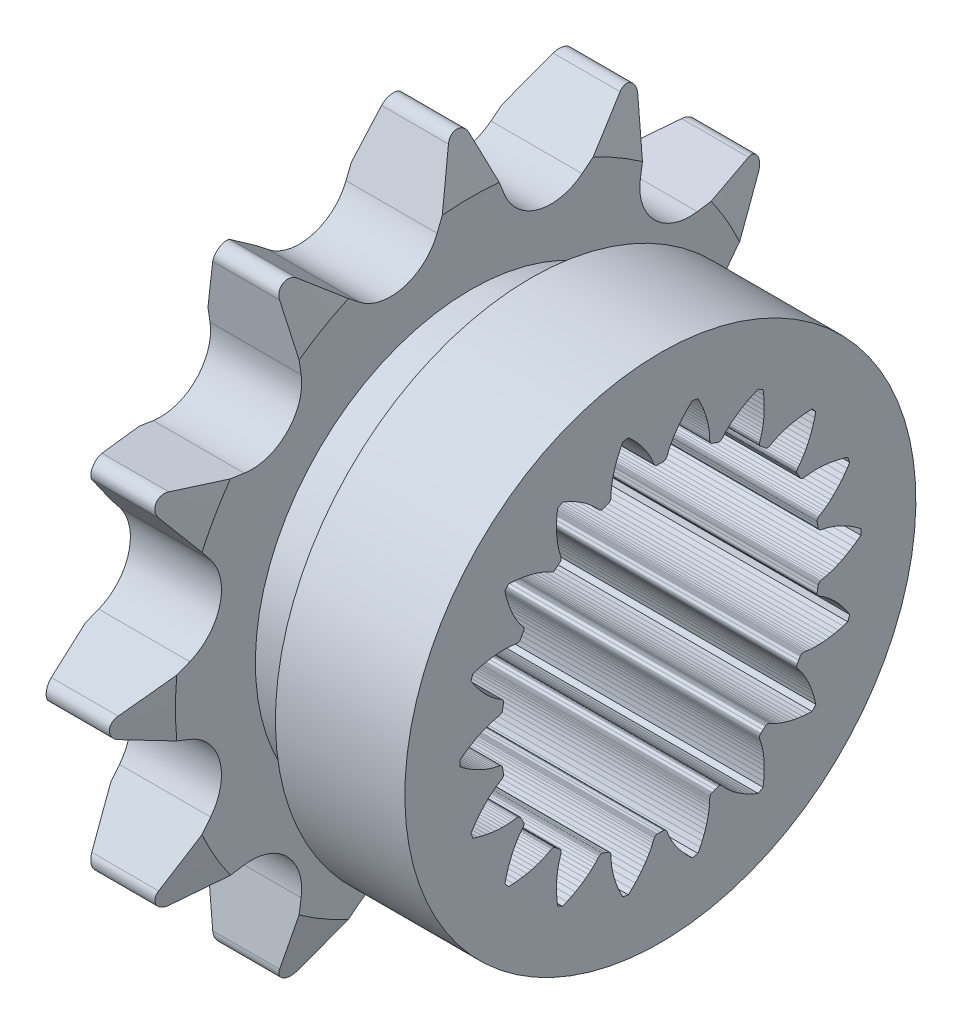
SolidWorks part; units mm, degrees
material "1144"
ref_plane "Front Plane" through (0, 0, 0) normal (0, 0, 1) x (1, 0, 0)
ref_plane "Top Plane" through (0, 0, 0) normal (0, 1, 0) x (1, 0, 0)
ref_plane "Right Plane" through (0, 0, 0) normal (1, 0, 0) x (0, 0, -1)
ref_axis "Axis1" through (-63.0158, 0, 0) along (1, 0, 0)
sketch "Sketch1" plane through (0, 0, 0) normal (0, 0, 1) x (1, 0, 0)
  line L0 (3.6068, 17.0561) -> (3.6068, 0) construction
  line L1 (22.225, 0) -> (22.225, 20.2311)
  line L3 (7.2136, 17.0561) -> (0, 17.0561)
  line L7 (0, 27.5082) -> (0, 30.0482) construction
  line L8 (0, 27.5082) -> (7.2136, 27.5082)
  line L9 (22.225, 0) -> (0, 0)
  line L10 (0, 0) -> (-84.1773, 0) construction
  line L11 (0, 17.0561) -> (0, 27.5082) construction
  line L12 (7.2136, 27.5082) -> (73.2462, 27.5082) construction
  line L13 (22.225, 0) -> (22.225, -20.2311) construction
  line L14 (3.6068, 0) -> (3.6068, -17.0561)
  line L15 (-15.4432, -17.0561) -> (22.6568, -17.0561)
  point P11 (0, 30.0482)
  dimension "D1" = 2.54
  dimension "hub_dia" = 40.4622
  dimension "width_teetth" = 7.2136
  dimension "D2" = 38.1
  dimension "length_thru" = 22.225
  dimension "OD" = 55.0164
  dimension "length_over_teeth" = 7.2136
  dimension "recess_hub_diam" = 34.1122
  dimension "hub_type" = 22.225
  dimension "projection 1" = 15.0114
  dimension "projection 2" = 0
sketch "Sketch2" plane through (0, 0, 0) normal (1, 0, 0) x (0, 0, -1)
  line L0 (0, 0) -> (0, 27.5082) construction
  line L1 (0, 0) -> (-13.7541, 23.8228) construction
  line L2 (0, 0) -> (-6.3502, 23.6991) construction
  line L3 (-0.8057, 26.9597) -> (-2.6638, 22.246)
  line L4 (-2.6638, 22.246) -> (-6.3502, 23.6991) construction
  line L5 (-0.8217, 27.4959) -> (0, 0) construction
  line L6 (-2.735, 27.3719) -> (0, 0) construction
  line L7 (-6.3502, 23.6991) -> (-2.4074, 24.0931) construction
  arc A1 (0, 27.5082) -> (-13.7541, 23.8228) centre (0, 0) ccw
  circle A2 centre (0, 0) radius 24.5351 construction
  circle A3 centre (-6.3502, 23.6991) radius 3.9624
  arc A4 (0, 27.5082) -> (-0.8057, 26.9597) centre (0, 26.6421) ccw
  dimension "pitch_diam" = 49.0703
  dimension "roller_diam" = 7.9248
  dimension "D1" = 1.712
  dimension "ang_1" = 30
  dimension "OD/2" = 27.5082
sketch "Taper Per Foot" plane through (0, 0, 0) normal (0, 0, 1) x (1, 0, 0)
  line L0 (22.225, 0) -> (22.225, 127)
  line L1 (22.225, 0) -> (22.225, 20.2311) construction
  line L2 (22.225, 127) -> (-282.575, 6.35)
  line L3 (-282.575, 6.35) -> (-282.575, 0)
  line L4 (-282.575, 0) -> (22.225, 0)
  line L5 (-282.575, 0) -> (-285.7823, 0) construction
  line L6 (-282.575, 6.35) -> (22.225, 6.35)
  line L7 (22.225, 6.35) -> (22.225, 127)
  dimension "1 Ft" = 304.8
  dimension "1 in" = 254
  dimension "Small End Diam" = 12.7
  dimension "Large End Diam" = 12.7
ref_plane "Plane1" through (7.2136, 0, 0) normal (1, 0, 0) x (0, 0, -1)
ref_plane "Plane2" through (7.2136, 0, 0) normal (1, 0, 0) x (0, 0, -1)
ref_plane "Plane3" through (0, 17.0561, 0) normal (-1, 0, 0) x (0, 0, 1)
ref_plane "Plane4" through (22.225, 0, 0) normal (1, 0, 0) x (0, 0, -1)
ref_plane "Plane5" through (3.6068, 0, 0) normal (1, 0, 0) x (0, 0, -1)
sketch "Sketch13" plane through (0, 0, 0) normal (0, 0, 1) x (1, 0, 0)
  line L0 (22.225, 0) -> (22.225, 20.2311) construction
  line L1 (0, 0) -> (22.225, 0)
  line L2 (0, 0) -> (0, 27.5082)
  line L3 (0, 27.5082) -> (22.225, 27.5082)
  line L4 (22.225, 0) -> (22.225, 27.5082)
revolve "Revolve1" add sketch "Sketch13" angle 360 about L10
sketch "Sketch6" plane through (0, -16.51, 0) normal (1, 0, 0) x (0, 0, -1)
  line L0 (-0.8057, 43.4697) -> (-2.6638, 38.756) construction
  line L1 (-0.8057, 43.4697) -> (-2.6638, 38.756)
  line L2 (-6.3502, 40.2091) -> (0, 16.51) construction
  line L3 (-12.7821, 40.2607) -> (-8.8161, 37.1075)
  arc A0 (0, 44.0182) -> (-0.8057, 43.4697) centre (0, 43.1521) ccw construction
  arc A1 (0, 44.0182) -> (-0.8057, 43.4697) centre (0, 43.1521) ccw
  arc A2 (-13.7541, 40.3328) -> (-12.7821, 40.2607) centre (-13.3211, 39.5828) cw
  arc A3 (-2.6638, 38.756) -> (-8.8161, 37.1075) centre (-6.3502, 40.2091) cw
  arc A4 (0, 44.0182) -> (-13.7541, 40.3328) centre (0, 16.51) ccw
extrude "Cut-Extrude1" cut sketch "Sketch6" along normal up to vertex (7.2136 mm away) up to point (7.2136, 17.0561, 0)
pattern_circular "CirPattern1" count 12 over 360 about axis through (-63.0158, 0, 0) along (1, 0, 0) of "Cut-Extrude1"
sketch "Sketch15" plane through (0, 0, 0) normal (0, 0, 1) x (1, 0, 0)
  line L1 (134.2136, 20.2311) -> (7.2136, 20.2311)
  line L2 (134.2136, 20.2311) -> (134.2136, 42.7482)
  line L3 (134.2136, 42.7482) -> (7.2136, 42.7482)
  line L4 (7.2136, 20.2311) -> (7.2136, 42.7482)
  line L5 (3.6068, 216.4797) -> (3.6068, 17.0561) construction
  line L6 (-127, 20.2311) -> (0, 20.2311)
  line L7 (0, 20.2311) -> (0, 42.7482)
  line L8 (-127, 42.7482) -> (0, 42.7482)
  line L9 (-127, 20.2311) -> (-127, 42.7482)
  dimension "D1" = 12.7
  dimension "D2" = 127
revolve "hub Cut-Revolve3" cut sketch "Sketch15" angle 360 about L10
sketch "Sketch4" plane through (0, 0, 0) normal (0, 0, 1) x (1, 0, 0)
  line L0 (0, 27.5082) -> (1.1045, 27.5082)
  line L2 (1.1045, 27.5082) -> (0, 23.3861)
  line L4 (0, 23.3861) -> (0, 27.5082)
  line L5 (3.6068, 27.5082) -> (3.6068, 44.9612) construction
  line L6 (7.2136, 27.5082) -> (6.1091, 27.5082)
  line L7 (7.2136, 23.3861) -> (7.2136, 27.5082)
  line L8 (6.1091, 27.5082) -> (7.2136, 23.3861)
  line L9 (0, 0) -> (-52.1231, 0) construction
  line L10 (0, 0) -> (-84.1773, 0) construction
  line L17 (0, 27.5082) -> (7.2136, 27.5082) construction
  dimension "D1" = 15
  dimension "D2" = 4.1221
revolve "Teeth Chamfer" cut sketch "Sketch4" angle 360 about L9
sketch "Sketch16" plane through (0, 0, 0) normal (0, 0, 1) x (1, 0, 0)
  line L1 (7.2136, 20.2311) -> (11.9761, 20.2311)
  line L2 (7.2136, 20.2311) -> (7.2136, 17.0561)
  line L3 (7.2136, 17.0561) -> (11.9761, 17.0561)
  line L4 (11.9761, 20.2311) -> (11.9761, 17.0561)
  line L5 (11.9761, 20.2311) -> (22.225, 20.2311) construction
  dimension "recess_width" = 4.7625
  dimension "recess_height" = 3.175
revolve "Recess" cut sketch "Sketch16" angle 360 about L10
sketch "Sketch32" plane through (22.225, 0, 0) normal (1, 0, 0) x (0, 0, -1)
  circle A1 centre (0, 0) radius 20.2311
  circle A2 centre (0, 0) radius 20.2311
  dimension "D1" = 0
extrude "Collar Reduction" [suppressed] cut sketch "Sketch32" against normal offset from surface (2.455 mm away) 19.77 up to face at (0, 0, 0)
ref_plane "Sprocket Teeth Center" through (3.6068, 0, 0) normal (-1, 0, 0) x (0, 0, 1)
sketch "Sketch35" plane through (3.6068, 0, 0) normal (1, 0, 0) x (0, 0, -1)
  circle A0 centre (0, 0) radius 24.5351 construction
  circle A1 centre (0, 0) radius 24.5351 construction
sketch "Sketch33" plane through (0, 0, 0) normal (-1, 0, 0) x (0, 0, 1)
  line L0 (14.7873, 4.9) -> (14.564, 4.5862)
  line L1 (14.564, 4.5862) -> (14.3413, 4.2995)
  line L2 (14.3413, 4.2995) -> (14.1194, 4.0373)
  line L3 (14.1194, 4.0373) -> (13.9032, 3.8025)
  line L4 (13.9032, 3.8025) -> (13.6912, 3.5908)
  line L5 (13.6912, 3.5908) -> (13.4871, 3.4033)
  line L6 (13.4871, 3.4033) -> (13.2928, 3.2393)
  line L7 (13.2928, 3.2393) -> (13.1069, 3.0953)
  line L8 (13.1069, 3.0953) -> (12.9349, 2.9732)
  line L9 (12.9349, 2.9732) -> (12.7748, 2.8693)
  line L10 (12.7748, 2.8693) -> (12.6452, 2.7922)
  line L11 (12.6452, 2.7922) -> (12.5432, 2.7214)
  line L12 (12.5432, 2.7214) -> (12.5028, 2.6848)
  line L13 (12.5028, 2.6848) -> (12.4694, 2.6479)
  line L14 (12.4694, 2.6479) -> (12.443, 2.611)
  line L15 (12.443, 2.611) -> (12.4236, 2.5742)
  line L16 (12.4236, 2.5742) -> (12.4112, 2.5378)
  line L17 (12.4112, 2.5378) -> (12.4058, 2.5022)
  line L18 (12.4058, 2.5022) -> (12.4072, 2.4677)
  line L19 (12.4072, 2.4677) -> (12.4155, 2.4245)
  line L20 (12.4155, 2.4245) -> (12.4578, 2.1966)
  line L21 (12.4578, 2.1966) -> (12.496, 1.9681)
  line L22 (12.496, 1.9681) -> (12.503, 1.9247)
  line L23 (12.503, 1.9247) -> (12.5134, 1.8917)
  line L24 (12.5134, 1.8917) -> (12.5307, 1.8601)
  line L25 (12.5307, 1.8601) -> (12.5548, 1.8302)
  line L26 (12.5548, 1.8302) -> (12.5856, 1.8023)
  line L27 (12.5856, 1.8023) -> (12.623, 1.7765)
  line L28 (12.623, 1.7765) -> (12.6671, 1.7533)
  line L29 (12.6671, 1.7533) -> (12.7175, 1.7328)
  line L30 (12.7175, 1.7328) -> (12.8375, 1.7011)
  line L31 (12.8375, 1.7011) -> (12.9858, 1.673)
  line L32 (12.9858, 1.673) -> (13.1717, 1.6301)
  line L33 (13.1717, 1.6301) -> (13.3751, 1.5742)
  line L34 (13.3751, 1.5742) -> (13.5991, 1.5025)
  line L35 (13.5991, 1.5025) -> (13.8378, 1.4148)
  line L36 (13.8378, 1.4148) -> (14.0937, 1.3085)
  line L37 (14.0937, 1.3085) -> (14.3653, 1.182)
  line L38 (14.3653, 1.182) -> (14.6487, 1.0353)
  line L39 (14.6487, 1.0353) -> (14.947, 0.8648)
  line L40 (14.947, 0.8648) -> (15.2543, 0.6715)
  line L41 (15.2543, 0.6715) -> (15.5714, 0.4531)
  line L42 (15.5714, 0.4531) -> (15.8734, 0.2265)
  line L43 (15.8734, -0.2265) -> (15.5714, -0.4531)
  line L44 (15.5714, -0.4531) -> (15.2543, -0.6715)
  line L45 (15.2543, -0.6715) -> (14.947, -0.8648)
  line L46 (14.947, -0.8648) -> (14.6487, -1.0353)
  line L47 (14.6487, -1.0353) -> (14.3653, -1.182)
  line L48 (14.3653, -1.182) -> (14.0937, -1.3085)
  line L49 (14.0937, -1.3085) -> (13.8378, -1.4148)
  line L50 (13.8378, -1.4148) -> (13.5991, -1.5025)
  line L51 (13.5991, -1.5025) -> (13.3751, -1.5742)
  line L52 (13.3751, -1.5742) -> (13.1717, -1.6301)
  line L53 (13.1717, -1.6301) -> (12.9858, -1.673)
  line L54 (12.9858, -1.673) -> (12.8375, -1.7011)
  line L55 (12.8375, -1.7011) -> (12.7175, -1.7328)
  line L56 (12.7175, -1.7328) -> (12.6671, -1.7533)
  line L57 (12.6671, -1.7533) -> (12.623, -1.7765)
  line L58 (12.623, -1.7765) -> (12.5856, -1.8023)
  line L59 (12.5856, -1.8023) -> (12.5548, -1.8302)
  line L60 (12.5548, -1.8302) -> (12.5307, -1.8601)
  line L61 (12.5307, -1.8601) -> (12.5134, -1.8917)
  line L62 (12.5134, -1.8917) -> (12.503, -1.9247)
  line L63 (12.503, -1.9247) -> (12.496, -1.9681)
  line L64 (12.496, -1.9681) -> (12.4578, -2.1966)
  line L65 (12.4578, -2.1966) -> (12.4155, -2.4245)
  line L66 (12.4155, -2.4245) -> (12.4072, -2.4677)
  line L67 (12.4072, -2.4677) -> (12.4058, -2.5022)
  line L68 (12.4058, -2.5022) -> (12.4112, -2.5378)
  line L69 (12.4112, -2.5378) -> (12.4236, -2.5742)
  line L70 (12.4236, -2.5742) -> (12.443, -2.611)
  line L71 (12.443, -2.611) -> (12.4694, -2.6479)
  line L72 (12.4694, -2.6479) -> (12.5028, -2.6848)
  line L73 (12.5028, -2.6848) -> (12.5432, -2.7214)
  line L74 (12.5432, -2.7214) -> (12.6452, -2.7922)
  line L75 (12.6452, -2.7922) -> (12.7748, -2.8693)
  line L76 (12.7748, -2.8693) -> (12.9349, -2.9732)
  line L77 (12.9349, -2.9732) -> (13.1069, -3.0953)
  line L78 (13.1069, -3.0953) -> (13.2928, -3.2393)
  line L79 (13.2928, -3.2393) -> (13.4871, -3.4033)
  line L80 (13.4871, -3.4033) -> (13.6912, -3.5908)
  line L81 (13.6912, -3.5908) -> (13.9032, -3.8025)
  line L82 (13.9032, -3.8025) -> (14.1194, -4.0373)
  line L83 (14.1194, -4.0373) -> (14.3413, -4.2995)
  line L84 (14.3413, -4.2995) -> (14.564, -4.5862)
  line L85 (14.564, -4.5862) -> (14.7873, -4.9)
  line L86 (14.7873, -4.9) -> (14.9936, -5.2162)
  line L87 (14.8386, -5.6419) -> (14.4773, -5.7515)
  line L88 (14.4773, -5.7515) -> (14.1046, -5.8483)
  line L89 (14.1046, -5.8483) -> (13.7498, -5.9248)
  line L90 (13.7498, -5.9248) -> (13.4112, -5.983)
  line L91 (13.4112, -5.983) -> (13.0947, -6.0239)
  line L92 (13.0947, -6.0239) -> (12.7962, -6.0499)
  line L93 (12.7962, -6.0499) -> (12.5194, -6.0623)
  line L94 (12.5194, -6.0623) -> (12.2651, -6.063)
  line L95 (12.2651, -6.063) -> (12.0301, -6.0539)
  line L96 (12.0301, -6.0539) -> (11.8198, -6.0368)
  line L97 (11.8198, -6.0368) -> (11.6305, -6.0135)
  line L98 (11.6305, -6.0135) -> (11.4815, -5.9892)
  line L99 (11.4815, -5.9892) -> (11.3579, -5.978)
  line L100 (11.3579, -5.978) -> (11.3035, -5.9799)
  line L101 (11.3035, -5.9799) -> (11.2542, -5.9867)
  line L102 (11.2542, -5.9867) -> (11.2102, -5.9981)
  line L103 (11.2102, -5.9981) -> (11.1717, -6.0138)
  line L104 (11.1717, -6.0138) -> (11.1388, -6.0337)
  line L105 (11.1388, -6.0337) -> (11.1118, -6.0574)
  line L106 (11.1118, -6.0574) -> (11.0907, -6.0849)
  line L107 (11.0907, -6.0849) -> (11.0693, -6.1233)
  line L108 (11.0693, -6.1233) -> (10.9552, -6.325)
  line L109 (10.9552, -6.325) -> (10.8376, -6.5247)
  line L110 (10.8376, -6.5247) -> (10.815, -6.5624)
  line L111 (10.815, -6.5624) -> (10.8018, -6.5944)
  line L112 (10.8018, -6.5944) -> (10.7947, -6.6297)
  line L113 (10.7947, -6.6297) -> (10.794, -6.668)
  line L114 (10.794, -6.668) -> (10.7996, -6.7092)
  line L115 (10.7996, -6.7092) -> (10.8117, -6.753)
  line L116 (10.8117, -6.753) -> (10.8305, -6.7991)
  line L117 (10.8305, -6.7991) -> (10.856, -6.8473)
  line L118 (10.856, -6.8473) -> (10.9276, -6.9487)
  line L119 (10.9276, -6.9487) -> (11.023, -7.0655)
  line L120 (11.023, -7.0655) -> (11.1379, -7.2178)
  line L121 (11.1379, -7.2178) -> (11.2578, -7.3915)
  line L122 (11.2578, -7.3915) -> (11.3833, -7.5904)
  line L123 (11.3833, -7.5904) -> (11.5098, -7.811)
  line L124 (11.5098, -7.811) -> (11.6374, -8.0569)
  line L125 (11.6374, -8.0569) -> (11.7642, -8.3284)
  line L126 (11.7642, -8.3284) -> (11.8871, -8.6229)
  line L127 (11.8871, -8.6229) -> (12.0059, -8.9453)
  line L128 (12.0059, -8.9453) -> (12.1171, -9.2908)
  line L129 (12.1171, -9.2908) -> (12.2196, -9.662)
  line L130 (12.2196, -9.662) -> (12.3053, -10.0297)
  line L131 (12.0141, -10.3767) -> (11.6371, -10.3562)
  line L132 (11.6371, -10.3562) -> (11.2538, -10.3197)
  line L133 (11.2538, -10.3197) -> (10.8942, -10.2702)
  line L134 (10.8942, -10.2702) -> (10.5561, -10.2091)
  line L135 (10.5561, -10.2091) -> (10.2447, -10.1393)
  line L136 (10.2447, -10.1393) -> (9.9553, -10.0616)
  line L137 (9.9553, -10.0616) -> (9.6909, -9.9785)
  line L138 (9.6909, -9.9785) -> (9.4517, -9.8923)
  line L139 (9.4517, -9.8923) -> (9.2341, -9.8033)
  line L140 (9.2341, -9.8033) -> (9.0423, -9.7154)
  line L141 (9.0423, -9.7154) -> (8.8723, -9.6287)
  line L142 (8.8723, -9.6287) -> (8.7407, -9.5549)
  line L143 (8.7407, -9.5549) -> (8.6284, -9.5021)
  line L144 (8.6284, -9.5021) -> (8.5765, -9.4853)
  line L145 (8.5765, -9.4853) -> (8.5279, -9.4748)
  line L146 (8.5279, -9.4748) -> (8.4826, -9.4705)
  line L147 (8.4826, -9.4705) -> (8.4411, -9.4721)
  line L148 (8.4411, -9.4721) -> (8.4034, -9.4795)
  line L149 (8.4034, -9.4795) -> (8.3699, -9.4926)
  line L150 (8.3699, -9.4926) -> (8.3407, -9.5111)
  line L151 (8.3407, -9.5111) -> (8.3074, -9.5399)
  line L152 (8.3074, -9.5399) -> (8.1313, -9.6905)
  line L153 (8.1313, -9.6905) -> (7.9524, -9.8378)
  line L154 (7.9524, -9.8378) -> (7.9183, -9.8655)
  line L155 (7.9183, -9.8655) -> (7.895, -9.8911)
  line L156 (7.895, -9.8911) -> (7.8763, -9.9219)
  line L157 (7.8763, -9.9219) -> (7.8624, -9.9577)
  line L158 (7.8624, -9.9577) -> (7.8536, -9.9983)
  line L159 (7.8536, -9.9983) -> (7.85, -10.0436)
  line L160 (7.85, -10.0436) -> (7.8519, -10.0933)
  line L161 (7.8519, -10.0933) -> (7.8594, -10.1473)
  line L162 (7.8594, -10.1473) -> (7.892, -10.2671)
  line L163 (7.892, -10.2671) -> (7.9417, -10.4095)
  line L164 (7.9417, -10.4095) -> (7.9976, -10.592)
  line L165 (7.9976, -10.592) -> (8.0509, -10.7961)
  line L166 (8.0509, -10.7961) -> (8.1007, -11.0259)
  line L167 (8.1007, -11.0259) -> (8.1441, -11.2765)
  line L168 (8.1441, -11.2765) -> (8.18, -11.5512)
  line L169 (8.18, -11.5512) -> (8.2063, -11.8497)
  line L170 (8.2063, -11.8497) -> (8.221, -12.1685)
  line L171 (8.221, -12.1685) -> (8.2224, -12.5121)
  line L172 (8.2224, -12.5121) -> (8.2087, -12.8748)
  line L173 (8.2087, -12.8748) -> (8.1781, -13.2587)
  line L174 (8.1781, -13.2587) -> (8.1329, -13.6335)
  line L175 (7.7405, -13.86) -> (7.3933, -13.7118)
  line L176 (7.3933, -13.7118) -> (7.0456, -13.5463)
  line L177 (7.0456, -13.5463) -> (6.7246, -13.3768)
  line L178 (6.7246, -13.3768) -> (6.4278, -13.2038)
  line L179 (6.4278, -13.2038) -> (6.159, -13.0317)
  line L180 (6.159, -13.0317) -> (5.9137, -12.8597)
  line L181 (5.9137, -12.8597) -> (5.6936, -12.6913)
  line L182 (5.6936, -12.6913) -> (5.4984, -12.5284)
  line L183 (5.4984, -12.5284) -> (5.3243, -12.3703)
  line L184 (5.3243, -12.3703) -> (5.1741, -12.2221)
  line L185 (5.1741, -12.2221) -> (5.0441, -12.0825)
  line L186 (5.0441, -12.0825) -> (4.9456, -11.9682)
  line L187 (4.9456, -11.9682) -> (4.8581, -11.8801)
  line L188 (4.8581, -11.8801) -> (4.8151, -11.8466)
  line L189 (4.8151, -11.8466) -> (4.773, -11.8201)
  line L190 (4.773, -11.8201) -> (4.732, -11.8006)
  line L191 (4.732, -11.8006) -> (4.6924, -11.7879)
  line L192 (4.6924, -11.7879) -> (4.6545, -11.782)
  line L193 (4.6545, -11.782) -> (4.6185, -11.7828)
  line L194 (4.6185, -11.7828) -> (4.5847, -11.7902)
  line L195 (4.5847, -11.7902) -> (4.5436, -11.8059)
  line L196 (4.5436, -11.8059) -> (4.3266, -11.8871)
  line L197 (4.3266, -11.8871) -> (4.1081, -11.9644)
  line L198 (4.1081, -11.9644) -> (4.0666, -11.9788)
  line L199 (4.0666, -11.9788) -> (4.0359, -11.9948)
  line L200 (4.0359, -11.9948) -> (4.0078, -12.0173)
  line L201 (4.0078, -12.0173) -> (3.9825, -12.0462)
  line L202 (3.9825, -12.0462) -> (3.9604, -12.0814)
  line L203 (3.9604, -12.0814) -> (3.9415, -12.1228)
  line L204 (3.9415, -12.1228) -> (3.9263, -12.1702)
  line L205 (3.9263, -12.1702) -> (3.9149, -12.2234)
  line L206 (3.9149, -12.2234) -> (3.9045, -12.3471)
  line L207 (3.9045, -12.3471) -> (3.9025, -12.498)
  line L208 (3.9025, -12.498) -> (3.8926, -12.6885)
  line L209 (3.8926, -12.6885) -> (3.8729, -12.8986)
  line L210 (3.8729, -12.8986) -> (3.8411, -13.1316)
  line L211 (3.8411, -13.1316) -> (3.7962, -13.3819)
  line L212 (3.7962, -13.3819) -> (3.7359, -13.6523)
  line L213 (3.7359, -13.6523) -> (3.6585, -13.9418)
  line L214 (3.6585, -13.9418) -> (3.5633, -14.2464)
  line L215 (3.5633, -14.2464) -> (3.4471, -14.5697)
  line L216 (3.4471, -14.5697) -> (3.3102, -14.9059)
  line L217 (3.3102, -14.9059) -> (3.1502, -15.2561)
  line L218 (3.1502, -15.2561) -> (2.9795, -15.5929)
  line L219 (2.5333, -15.6716) -> (2.2577, -15.4135)
  line L220 (2.2577, -15.4135) -> (1.9875, -15.1391)
  line L221 (1.9875, -15.1391) -> (1.7439, -14.8701)
  line L222 (1.7439, -14.8701) -> (1.5241, -14.606)
  line L223 (1.5241, -14.606) -> (1.3305, -14.3523)
  line L224 (1.3305, -14.3523) -> (1.1587, -14.1068)
  line L225 (1.1587, -14.1068) -> (1.0096, -13.8732)
  line L226 (1.0096, -13.8732) -> (0.8818, -13.6534)
  line L227 (0.8818, -13.6534) -> (0.7723, -13.4453)
  line L228 (0.7723, -13.4453) -> (0.6819, -13.2547)
  line L229 (0.6819, -13.2547) -> (0.6074, -13.079)
  line L230 (0.6074, -13.079) -> (0.554, -12.9379)
  line L231 (0.554, -12.9379) -> (0.5019, -12.8252)
  line L232 (0.5019, -12.8252) -> (0.4729, -12.7791)
  line L233 (0.4729, -12.7791) -> (0.4424, -12.7398)
  line L234 (0.4424, -12.7398) -> (0.4106, -12.7074)
  line L235 (0.4106, -12.7074) -> (0.3777, -12.6819)
  line L236 (0.3777, -12.6819) -> (0.3441, -12.6633)
  line L237 (0.3441, -12.6633) -> (0.31, -12.6518)
  line L238 (0.31, -12.6518) -> (0.2757, -12.6472)
  line L239 (0.2757, -12.6472) -> (0.2317, -12.6479)
  line L240 (0.2317, -12.6479) -> (0, -12.65)
  line L241 (0, -12.65) -> (-0.2317, -12.6479)
  line L242 (-0.2317, -12.6479) -> (-0.2757, -12.6472)
  line L243 (-0.2757, -12.6472) -> (-0.31, -12.6518)
  line L244 (-0.31, -12.6518) -> (-0.3441, -12.6633)
  line L245 (-0.3441, -12.6633) -> (-0.3777, -12.6819)
  line L246 (-0.3777, -12.6819) -> (-0.4106, -12.7074)
  line L247 (-0.4106, -12.7074) -> (-0.4424, -12.7398)
  line L248 (-0.4424, -12.7398) -> (-0.4729, -12.7791)
  line L249 (-0.4729, -12.7791) -> (-0.5019, -12.8252)
  line L250 (-0.5019, -12.8252) -> (-0.554, -12.9379)
  line L251 (-0.554, -12.9379) -> (-0.6074, -13.079)
  line L252 (-0.6074, -13.079) -> (-0.6819, -13.2547)
  line L253 (-0.6819, -13.2547) -> (-0.7723, -13.4453)
  line L254 (-0.7723, -13.4453) -> (-0.8818, -13.6534)
  line L255 (-0.8818, -13.6534) -> (-1.0096, -13.8732)
  line L256 (-1.0096, -13.8732) -> (-1.1587, -14.1068)
  line L257 (-1.1587, -14.1068) -> (-1.3305, -14.3523)
  line L258 (-1.3305, -14.3523) -> (-1.5241, -14.606)
  line L259 (-1.5241, -14.606) -> (-1.7439, -14.8701)
  line L260 (-1.7439, -14.8701) -> (-1.9875, -15.1391)
  line L261 (-1.9875, -15.1391) -> (-2.2577, -15.4135)
  line L262 (-2.2577, -15.4135) -> (-2.5333, -15.6716)
  line L263 (-2.9795, -15.5929) -> (-3.1502, -15.2561)
  line L264 (-3.1502, -15.2561) -> (-3.3102, -14.9059)
  line L265 (-3.3102, -14.9059) -> (-3.4471, -14.5697)
  line L266 (-3.4471, -14.5697) -> (-3.5633, -14.2464)
  line L267 (-3.5633, -14.2464) -> (-3.6585, -13.9418)
  line L268 (-3.6585, -13.9418) -> (-3.7359, -13.6523)
  line L269 (-3.7359, -13.6523) -> (-3.7962, -13.3819)
  line L270 (-3.7962, -13.3819) -> (-3.8411, -13.1316)
  line L271 (-3.8411, -13.1316) -> (-3.8729, -12.8986)
  line L272 (-3.8729, -12.8986) -> (-3.8926, -12.6885)
  line L273 (-3.8926, -12.6885) -> (-3.9025, -12.498)
  line L274 (-3.9025, -12.498) -> (-3.9045, -12.3471)
  line L275 (-3.9045, -12.3471) -> (-3.9149, -12.2234)
  line L276 (-3.9149, -12.2234) -> (-3.9263, -12.1702)
  line L277 (-3.9263, -12.1702) -> (-3.9415, -12.1228)
  line L278 (-3.9415, -12.1228) -> (-3.9604, -12.0814)
  line L279 (-3.9604, -12.0814) -> (-3.9825, -12.0462)
  line L280 (-3.9825, -12.0462) -> (-4.0078, -12.0173)
  line L281 (-4.0078, -12.0173) -> (-4.0359, -11.9948)
  line L282 (-4.0359, -11.9948) -> (-4.0666, -11.9788)
  line L283 (-4.0666, -11.9788) -> (-4.1081, -11.9644)
  line L284 (-4.1081, -11.9644) -> (-4.3266, -11.8871)
  line L285 (-4.3266, -11.8871) -> (-4.5436, -11.8059)
  line L286 (-4.5436, -11.8059) -> (-4.5847, -11.7902)
  line L287 (-4.5847, -11.7902) -> (-4.6185, -11.7828)
  line L288 (-4.6185, -11.7828) -> (-4.6545, -11.782)
  line L289 (-4.6545, -11.782) -> (-4.6924, -11.7879)
  line L290 (-4.6924, -11.7879) -> (-4.732, -11.8006)
  line L291 (-4.732, -11.8006) -> (-4.773, -11.8201)
  line L292 (-4.773, -11.8201) -> (-4.8151, -11.8466)
  line L293 (-4.8151, -11.8466) -> (-4.8581, -11.8801)
  line L294 (-4.8581, -11.8801) -> (-4.9456, -11.9682)
  line L295 (-4.9456, -11.9682) -> (-5.0441, -12.0825)
  line L296 (-5.0441, -12.0825) -> (-5.1741, -12.2221)
  line L297 (-5.1741, -12.2221) -> (-5.3243, -12.3703)
  line L298 (-5.3243, -12.3703) -> (-5.4984, -12.5284)
  line L299 (-5.4984, -12.5284) -> (-5.6936, -12.6913)
  line L300 (-5.6936, -12.6913) -> (-5.9137, -12.8597)
  line L301 (-5.9137, -12.8597) -> (-6.159, -13.0317)
  line L302 (-6.159, -13.0317) -> (-6.4278, -13.2038)
  line L303 (-6.4278, -13.2038) -> (-6.7246, -13.3768)
  line L304 (-6.7246, -13.3768) -> (-7.0456, -13.5463)
  line L305 (-7.0456, -13.5463) -> (-7.3933, -13.7118)
  line L306 (-7.3933, -13.7118) -> (-7.7405, -13.86)
  line L307 (-8.1329, -13.6335) -> (-8.1781, -13.2587)
  line L308 (-8.1781, -13.2587) -> (-8.2087, -12.8748)
  line L309 (-8.2087, -12.8748) -> (-8.2224, -12.5121)
  line L310 (-8.2224, -12.5121) -> (-8.221, -12.1685)
  line L311 (-8.221, -12.1685) -> (-8.2063, -11.8497)
  line L312 (-8.2063, -11.8497) -> (-8.18, -11.5512)
  line L313 (-8.18, -11.5512) -> (-8.1441, -11.2765)
  line L314 (-8.1441, -11.2765) -> (-8.1007, -11.0259)
  line L315 (-8.1007, -11.0259) -> (-8.0509, -10.7961)
  line L316 (-8.0509, -10.7961) -> (-7.9976, -10.592)
  line L317 (-7.9976, -10.592) -> (-7.9417, -10.4095)
  line L318 (-7.9417, -10.4095) -> (-7.892, -10.2671)
  line L319 (-7.892, -10.2671) -> (-7.8594, -10.1473)
  line L320 (-7.8594, -10.1473) -> (-7.8519, -10.0933)
  line L321 (-7.8519, -10.0933) -> (-7.85, -10.0436)
  line L322 (-7.85, -10.0436) -> (-7.8536, -9.9983)
  line L323 (-7.8536, -9.9983) -> (-7.8624, -9.9577)
  line L324 (-7.8624, -9.9577) -> (-7.8763, -9.9219)
  line L325 (-7.8763, -9.9219) -> (-7.895, -9.8911)
  line L326 (-7.895, -9.8911) -> (-7.9183, -9.8655)
  line L327 (-7.9183, -9.8655) -> (-7.9524, -9.8378)
  line L328 (-7.9524, -9.8378) -> (-8.1313, -9.6905)
  line L329 (-8.1313, -9.6905) -> (-8.3074, -9.5399)
  line L330 (-8.3074, -9.5399) -> (-8.3407, -9.5111)
  line L331 (-8.3407, -9.5111) -> (-8.3699, -9.4926)
  line L332 (-8.3699, -9.4926) -> (-8.4034, -9.4795)
  line L333 (-8.4034, -9.4795) -> (-8.4411, -9.4721)
  line L334 (-8.4411, -9.4721) -> (-8.4826, -9.4705)
  line L335 (-8.4826, -9.4705) -> (-8.5279, -9.4748)
  line L336 (-8.5279, -9.4748) -> (-8.5765, -9.4853)
  line L337 (-8.5765, -9.4853) -> (-8.6284, -9.5021)
  line L338 (-8.6284, -9.5021) -> (-8.7407, -9.5549)
  line L339 (-8.7407, -9.5549) -> (-8.8723, -9.6287)
  line L340 (-8.8723, -9.6287) -> (-9.0423, -9.7154)
  line L341 (-9.0423, -9.7154) -> (-9.2341, -9.8033)
  line L342 (-9.2341, -9.8033) -> (-9.4517, -9.8923)
  line L343 (-9.4517, -9.8923) -> (-9.6909, -9.9785)
  line L344 (-9.6909, -9.9785) -> (-9.9553, -10.0616)
  line L345 (-9.9553, -10.0616) -> (-10.2447, -10.1393)
  line L346 (-10.2447, -10.1393) -> (-10.5561, -10.2091)
  line L347 (-10.5561, -10.2091) -> (-10.8942, -10.2702)
  line L348 (-10.8942, -10.2702) -> (-11.2538, -10.3197)
  line L349 (-11.2538, -10.3197) -> (-11.6371, -10.3562)
  line L350 (-11.6371, -10.3562) -> (-12.0141, -10.3767)
  line L351 (-12.3053, -10.0297) -> (-12.2196, -9.662)
  line L352 (-12.2196, -9.662) -> (-12.1171, -9.2908)
  line L353 (-12.1171, -9.2908) -> (-12.0059, -8.9453)
  line L354 (-12.0059, -8.9453) -> (-11.8871, -8.6229)
  line L355 (-11.8871, -8.6229) -> (-11.7642, -8.3284)
  line L356 (-11.7642, -8.3284) -> (-11.6374, -8.0569)
  line L357 (-11.6374, -8.0569) -> (-11.5098, -7.811)
  line L358 (-11.5098, -7.811) -> (-11.3833, -7.5904)
  line L359 (-11.3833, -7.5904) -> (-11.2578, -7.3915)
  line L360 (-11.2578, -7.3915) -> (-11.1379, -7.2178)
  line L361 (-11.1379, -7.2178) -> (-11.023, -7.0655)
  line L362 (-11.023, -7.0655) -> (-10.9276, -6.9487)
  line L363 (-10.9276, -6.9487) -> (-10.856, -6.8473)
  line L364 (-10.856, -6.8473) -> (-10.8305, -6.7991)
  line L365 (-10.8305, -6.7991) -> (-10.8117, -6.753)
  line L366 (-10.8117, -6.753) -> (-10.7996, -6.7092)
  line L367 (-10.7996, -6.7092) -> (-10.794, -6.668)
  line L368 (-10.794, -6.668) -> (-10.7947, -6.6297)
  line L369 (-10.7947, -6.6297) -> (-10.8018, -6.5944)
  line L370 (-10.8018, -6.5944) -> (-10.815, -6.5624)
  line L371 (-10.815, -6.5624) -> (-10.8376, -6.5247)
  line L372 (-10.8376, -6.5247) -> (-10.9552, -6.325)
  line L373 (-10.9552, -6.325) -> (-11.0693, -6.1233)
  line L374 (-11.0693, -6.1233) -> (-11.0907, -6.0849)
  line L375 (-11.0907, -6.0849) -> (-11.1118, -6.0574)
  line L376 (-11.1118, -6.0574) -> (-11.1388, -6.0337)
  line L377 (-11.1388, -6.0337) -> (-11.1717, -6.0138)
  line L378 (-11.1717, -6.0138) -> (-11.2102, -5.9981)
  line L379 (-11.2102, -5.9981) -> (-11.2542, -5.9867)
  line L380 (-11.2542, -5.9867) -> (-11.3035, -5.9799)
  line L381 (-11.3035, -5.9799) -> (-11.3579, -5.978)
  line L382 (-11.3579, -5.978) -> (-11.4815, -5.9892)
  line L383 (-11.4815, -5.9892) -> (-11.6305, -6.0135)
  line L384 (-11.6305, -6.0135) -> (-11.8198, -6.0368)
  line L385 (-11.8198, -6.0368) -> (-12.0301, -6.0539)
  line L386 (-12.0301, -6.0539) -> (-12.2651, -6.063)
  line L387 (-12.2651, -6.063) -> (-12.5194, -6.0623)
  line L388 (-12.5194, -6.0623) -> (-12.7962, -6.0499)
  line L389 (-12.7962, -6.0499) -> (-13.0947, -6.0239)
  line L390 (-13.0947, -6.0239) -> (-13.4112, -5.983)
  line L391 (-13.4112, -5.983) -> (-13.7498, -5.9248)
  line L392 (-13.7498, -5.9248) -> (-14.1046, -5.8483)
  line L393 (-14.1046, -5.8483) -> (-14.4773, -5.7515)
  line L394 (-14.4773, -5.7515) -> (-14.8386, -5.6419)
  line L395 (-14.9936, -5.2162) -> (-14.7873, -4.9)
  line L396 (-14.7873, -4.9) -> (-14.564, -4.5862)
  line L397 (-14.564, -4.5862) -> (-14.3413, -4.2995)
  line L398 (-14.3413, -4.2995) -> (-14.1194, -4.0373)
  line L399 (-14.1194, -4.0373) -> (-13.9032, -3.8025)
  line L400 (-13.9032, -3.8025) -> (-13.6912, -3.5908)
  line L401 (-13.6912, -3.5908) -> (-13.4871, -3.4033)
  line L402 (-13.4871, -3.4033) -> (-13.2928, -3.2393)
  line L403 (-13.2928, -3.2393) -> (-13.1069, -3.0953)
  line L404 (-13.1069, -3.0953) -> (-12.9349, -2.9732)
  line L405 (-12.9349, -2.9732) -> (-12.7748, -2.8693)
  line L406 (-12.7748, -2.8693) -> (-12.6452, -2.7922)
  line L407 (-12.6452, -2.7922) -> (-12.5432, -2.7214)
  line L408 (-12.5432, -2.7214) -> (-12.5028, -2.6848)
  line L409 (-12.5028, -2.6848) -> (-12.4694, -2.6479)
  line L410 (-12.4694, -2.6479) -> (-12.443, -2.611)
  line L411 (-12.443, -2.611) -> (-12.4236, -2.5742)
  line L412 (-12.4236, -2.5742) -> (-12.4112, -2.5378)
  line L413 (-12.4112, -2.5378) -> (-12.4058, -2.5022)
  line L414 (-12.4058, -2.5022) -> (-12.4072, -2.4677)
  line L415 (-12.4072, -2.4677) -> (-12.4155, -2.4245)
  line L416 (-12.4155, -2.4245) -> (-12.4578, -2.1966)
  line L417 (-12.4578, -2.1966) -> (-12.496, -1.9681)
  line L418 (-12.496, -1.9681) -> (-12.503, -1.9247)
  line L419 (-12.503, -1.9247) -> (-12.5134, -1.8917)
  line L420 (-12.5134, -1.8917) -> (-12.5307, -1.8601)
  line L421 (-12.5307, -1.8601) -> (-12.5548, -1.8302)
  line L422 (-12.5548, -1.8302) -> (-12.5856, -1.8023)
  line L423 (-12.5856, -1.8023) -> (-12.623, -1.7765)
  line L424 (-12.623, -1.7765) -> (-12.6671, -1.7533)
  line L425 (-12.6671, -1.7533) -> (-12.7175, -1.7328)
  line L426 (-12.7175, -1.7328) -> (-12.8375, -1.7011)
  line L427 (-12.8375, -1.7011) -> (-12.9858, -1.673)
  line L428 (-12.9858, -1.673) -> (-13.1717, -1.6301)
  line L429 (-13.1717, -1.6301) -> (-13.3751, -1.5742)
  line L430 (-13.3751, -1.5742) -> (-13.5991, -1.5025)
  line L431 (-13.5991, -1.5025) -> (-13.8378, -1.4148)
  line L432 (-13.8378, -1.4148) -> (-14.0937, -1.3085)
  line L433 (-14.0937, -1.3085) -> (-14.3653, -1.182)
  line L434 (-14.3653, -1.182) -> (-14.6487, -1.0353)
  line L435 (-14.6487, -1.0353) -> (-14.947, -0.8648)
  line L436 (-14.947, -0.8648) -> (-15.2543, -0.6715)
  line L437 (-15.2543, -0.6715) -> (-15.5714, -0.4531)
  line L438 (-15.5714, -0.4531) -> (-15.8734, -0.2265)
  line L439 (-15.8734, 0.2265) -> (-15.5714, 0.4531)
  line L440 (-15.5714, 0.4531) -> (-15.2543, 0.6715)
  line L441 (-15.2543, 0.6715) -> (-14.947, 0.8648)
  line L442 (-14.947, 0.8648) -> (-14.6487, 1.0353)
  line L443 (-14.6487, 1.0353) -> (-14.3653, 1.182)
  line L444 (-14.3653, 1.182) -> (-14.0937, 1.3085)
  line L445 (-14.0937, 1.3085) -> (-13.8378, 1.4148)
  line L446 (-13.8378, 1.4148) -> (-13.5991, 1.5025)
  line L447 (-13.5991, 1.5025) -> (-13.3751, 1.5742)
  line L448 (-13.3751, 1.5742) -> (-13.1717, 1.6301)
  line L449 (-13.1717, 1.6301) -> (-12.9858, 1.673)
  line L450 (-12.9858, 1.673) -> (-12.8375, 1.7011)
  line L451 (-12.8375, 1.7011) -> (-12.7175, 1.7328)
  line L452 (-12.7175, 1.7328) -> (-12.6671, 1.7533)
  line L453 (-12.6671, 1.7533) -> (-12.623, 1.7765)
  line L454 (-12.623, 1.7765) -> (-12.5856, 1.8023)
  line L455 (-12.5856, 1.8023) -> (-12.5548, 1.8302)
  line L456 (-12.5548, 1.8302) -> (-12.5307, 1.8601)
  line L457 (-12.5307, 1.8601) -> (-12.5134, 1.8917)
  line L458 (-12.5134, 1.8917) -> (-12.503, 1.9247)
  line L459 (-12.503, 1.9247) -> (-12.496, 1.9681)
  line L460 (-12.496, 1.9681) -> (-12.4578, 2.1966)
  line L461 (-12.4578, 2.1966) -> (-12.4155, 2.4245)
  line L462 (-12.4155, 2.4245) -> (-12.4072, 2.4677)
  line L463 (-12.4072, 2.4677) -> (-12.4058, 2.5022)
  line L464 (-12.4058, 2.5022) -> (-12.4112, 2.5378)
  line L465 (-12.4112, 2.5378) -> (-12.4236, 2.5742)
  line L466 (-12.4236, 2.5742) -> (-12.443, 2.611)
  line L467 (-12.443, 2.611) -> (-12.4694, 2.6479)
  line L468 (-12.4694, 2.6479) -> (-12.5028, 2.6848)
  line L469 (-12.5028, 2.6848) -> (-12.5432, 2.7214)
  line L470 (-12.5432, 2.7214) -> (-12.6452, 2.7922)
  line L471 (-12.6452, 2.7922) -> (-12.7748, 2.8693)
  line L472 (-12.7748, 2.8693) -> (-12.9349, 2.9732)
  line L473 (-12.9349, 2.9732) -> (-13.1069, 3.0953)
  line L474 (-13.1069, 3.0953) -> (-13.2928, 3.2393)
  line L475 (-13.2928, 3.2393) -> (-13.4871, 3.4033)
  line L476 (-13.4871, 3.4033) -> (-13.6912, 3.5908)
  line L477 (-13.6912, 3.5908) -> (-13.9032, 3.8025)
  line L478 (-13.9032, 3.8025) -> (-14.1194, 4.0373)
  line L479 (-14.1194, 4.0373) -> (-14.3413, 4.2995)
  line L480 (-14.3413, 4.2995) -> (-14.564, 4.5862)
  line L481 (-14.564, 4.5862) -> (-14.7873, 4.9)
  line L482 (-14.7873, 4.9) -> (-14.9936, 5.2162)
  line L483 (-14.8386, 5.6419) -> (-14.4773, 5.7515)
  line L484 (-14.4773, 5.7515) -> (-14.1046, 5.8483)
  line L485 (-14.1046, 5.8483) -> (-13.7498, 5.9248)
  line L486 (-13.7498, 5.9248) -> (-13.4112, 5.983)
  line L487 (-13.4112, 5.983) -> (-13.0947, 6.0239)
  line L488 (-13.0947, 6.0239) -> (-12.7962, 6.0499)
  line L489 (-12.7962, 6.0499) -> (-12.5194, 6.0623)
  line L490 (-12.5194, 6.0623) -> (-12.2651, 6.063)
  line L491 (-12.2651, 6.063) -> (-12.0301, 6.0539)
  line L492 (-12.0301, 6.0539) -> (-11.8198, 6.0368)
  line L493 (-11.8198, 6.0368) -> (-11.6305, 6.0135)
  line L494 (-11.6305, 6.0135) -> (-11.4815, 5.9892)
  line L495 (-11.4815, 5.9892) -> (-11.3579, 5.978)
  line L496 (-11.3579, 5.978) -> (-11.3035, 5.9799)
  line L497 (-11.3035, 5.9799) -> (-11.2542, 5.9867)
  line L498 (-11.2542, 5.9867) -> (-11.2102, 5.9981)
  line L499 (-11.2102, 5.9981) -> (-11.1717, 6.0138)
  line L500 (-11.1717, 6.0138) -> (-11.1388, 6.0337)
  line L501 (-11.1388, 6.0337) -> (-11.1118, 6.0574)
  line L502 (-11.1118, 6.0574) -> (-11.0907, 6.0849)
  line L503 (-11.0907, 6.0849) -> (-11.0693, 6.1233)
  line L504 (-11.0693, 6.1233) -> (-10.9552, 6.325)
  line L505 (-10.9552, 6.325) -> (-10.8376, 6.5247)
  line L506 (-10.8376, 6.5247) -> (-10.815, 6.5624)
  line L507 (-10.815, 6.5624) -> (-10.8018, 6.5944)
  line L508 (-10.8018, 6.5944) -> (-10.7947, 6.6297)
  line L509 (-10.7947, 6.6297) -> (-10.794, 6.668)
  line L510 (-10.794, 6.668) -> (-10.7996, 6.7092)
  line L511 (-10.7996, 6.7092) -> (-10.8117, 6.753)
  line L512 (-10.8117, 6.753) -> (-10.8305, 6.7991)
  line L513 (-10.8305, 6.7991) -> (-10.856, 6.8473)
  line L514 (-10.856, 6.8473) -> (-10.9276, 6.9487)
  line L515 (-10.9276, 6.9487) -> (-11.023, 7.0655)
  line L516 (-11.023, 7.0655) -> (-11.1379, 7.2178)
  line L517 (-11.1379, 7.2178) -> (-11.2578, 7.3915)
  line L518 (-11.2578, 7.3915) -> (-11.3833, 7.5904)
  line L519 (-11.3833, 7.5904) -> (-11.5098, 7.811)
  line L520 (-11.5098, 7.811) -> (-11.6374, 8.0569)
  line L521 (-11.6374, 8.0569) -> (-11.7642, 8.3284)
  line L522 (-11.7642, 8.3284) -> (-11.8871, 8.6229)
  line L523 (-11.8871, 8.6229) -> (-12.0059, 8.9453)
  line L524 (-12.0059, 8.9453) -> (-12.1171, 9.2908)
  line L525 (-12.1171, 9.2908) -> (-12.2196, 9.662)
  line L526 (-12.2196, 9.662) -> (-12.3053, 10.0297)
  line L527 (-12.0141, 10.3767) -> (-11.6371, 10.3562)
  line L528 (-11.6371, 10.3562) -> (-11.2538, 10.3197)
  line L529 (-11.2538, 10.3197) -> (-10.8942, 10.2702)
  line L530 (-10.8942, 10.2702) -> (-10.5561, 10.2091)
  line L531 (-10.5561, 10.2091) -> (-10.2447, 10.1393)
  line L532 (-10.2447, 10.1393) -> (-9.9553, 10.0616)
  line L533 (-9.9553, 10.0616) -> (-9.6909, 9.9785)
  line L534 (-9.6909, 9.9785) -> (-9.4517, 9.8923)
  line L535 (-9.4517, 9.8923) -> (-9.2341, 9.8033)
  line L536 (-9.2341, 9.8033) -> (-9.0423, 9.7154)
  line L537 (-9.0423, 9.7154) -> (-8.8723, 9.6287)
  line L538 (-8.8723, 9.6287) -> (-8.7407, 9.5549)
  line L539 (-8.7407, 9.5549) -> (-8.6284, 9.5021)
  line L540 (-8.6284, 9.5021) -> (-8.5765, 9.4853)
  line L541 (-8.5765, 9.4853) -> (-8.5279, 9.4748)
  line L542 (-8.5279, 9.4748) -> (-8.4826, 9.4705)
  line L543 (-8.4826, 9.4705) -> (-8.4411, 9.4721)
  line L544 (-8.4411, 9.4721) -> (-8.4034, 9.4795)
  line L545 (-8.4034, 9.4795) -> (-8.3699, 9.4926)
  line L546 (-8.3699, 9.4926) -> (-8.3407, 9.5111)
  line L547 (-8.3407, 9.5111) -> (-8.3074, 9.5399)
  line L548 (-8.3074, 9.5399) -> (-8.1313, 9.6905)
  line L549 (-8.1313, 9.6905) -> (-7.9524, 9.8378)
  line L550 (-7.9524, 9.8378) -> (-7.9183, 9.8655)
  line L551 (-7.9183, 9.8655) -> (-7.895, 9.8911)
  line L552 (-7.895, 9.8911) -> (-7.8763, 9.9219)
  line L553 (-7.8763, 9.9219) -> (-7.8624, 9.9577)
  line L554 (-7.8624, 9.9577) -> (-7.8536, 9.9983)
  line L555 (-7.8536, 9.9983) -> (-7.85, 10.0436)
  line L556 (-7.85, 10.0436) -> (-7.8519, 10.0933)
  line L557 (-7.8519, 10.0933) -> (-7.8594, 10.1473)
  line L558 (-7.8594, 10.1473) -> (-7.892, 10.2671)
  line L559 (-7.892, 10.2671) -> (-7.9417, 10.4095)
  line L560 (-7.9417, 10.4095) -> (-7.9976, 10.592)
  line L561 (-7.9976, 10.592) -> (-8.0509, 10.7961)
  line L562 (-8.0509, 10.7961) -> (-8.1007, 11.0259)
  line L563 (-8.1007, 11.0259) -> (-8.1441, 11.2765)
  line L564 (-8.1441, 11.2765) -> (-8.18, 11.5512)
  line L565 (-8.18, 11.5512) -> (-8.2063, 11.8497)
  line L566 (-8.2063, 11.8497) -> (-8.221, 12.1685)
  line L567 (-8.221, 12.1685) -> (-8.2224, 12.5121)
  line L568 (-8.2224, 12.5121) -> (-8.2087, 12.8748)
  line L569 (-8.2087, 12.8748) -> (-8.1781, 13.2587)
  line L570 (-8.1781, 13.2587) -> (-8.1329, 13.6335)
  line L571 (-7.7405, 13.86) -> (-7.3933, 13.7118)
  line L572 (-7.3933, 13.7118) -> (-7.0456, 13.5463)
  line L573 (-7.0456, 13.5463) -> (-6.7246, 13.3768)
  line L574 (-6.7246, 13.3768) -> (-6.4278, 13.2038)
  line L575 (-6.4278, 13.2038) -> (-6.159, 13.0317)
  line L576 (-6.159, 13.0317) -> (-5.9137, 12.8597)
  line L577 (-5.9137, 12.8597) -> (-5.6936, 12.6913)
  line L578 (-5.6936, 12.6913) -> (-5.4984, 12.5284)
  line L579 (-5.4984, 12.5284) -> (-5.3243, 12.3703)
  line L580 (-5.3243, 12.3703) -> (-5.1741, 12.2221)
  line L581 (-5.1741, 12.2221) -> (-5.0441, 12.0825)
  line L582 (-5.0441, 12.0825) -> (-4.9456, 11.9682)
  line L583 (-4.9456, 11.9682) -> (-4.8581, 11.8801)
  line L584 (-4.8581, 11.8801) -> (-4.8151, 11.8466)
  line L585 (-4.8151, 11.8466) -> (-4.773, 11.8201)
  line L586 (-4.773, 11.8201) -> (-4.732, 11.8006)
  line L587 (-4.732, 11.8006) -> (-4.6924, 11.7879)
  line L588 (-4.6924, 11.7879) -> (-4.6545, 11.782)
  line L589 (-4.6545, 11.782) -> (-4.6185, 11.7828)
  line L590 (-4.6185, 11.7828) -> (-4.5847, 11.7902)
  line L591 (-4.5847, 11.7902) -> (-4.5436, 11.8059)
  line L592 (-4.5436, 11.8059) -> (-4.3266, 11.8871)
  line L593 (-4.3266, 11.8871) -> (-4.1081, 11.9644)
  line L594 (-4.1081, 11.9644) -> (-4.0666, 11.9788)
  line L595 (-4.0666, 11.9788) -> (-4.0359, 11.9948)
  line L596 (-4.0359, 11.9948) -> (-4.0078, 12.0173)
  line L597 (-4.0078, 12.0173) -> (-3.9825, 12.0462)
  line L598 (-3.9825, 12.0462) -> (-3.9604, 12.0814)
  line L599 (-3.9604, 12.0814) -> (-3.9415, 12.1228)
  line L600 (-3.9415, 12.1228) -> (-3.9263, 12.1702)
  line L601 (-3.9263, 12.1702) -> (-3.9149, 12.2234)
  line L602 (-3.9149, 12.2234) -> (-3.9045, 12.3471)
  line L603 (-3.9045, 12.3471) -> (-3.9025, 12.498)
  line L604 (-3.9025, 12.498) -> (-3.8926, 12.6885)
  line L605 (-3.8926, 12.6885) -> (-3.8729, 12.8986)
  line L606 (-3.8729, 12.8986) -> (-3.8411, 13.1316)
  line L607 (-3.8411, 13.1316) -> (-3.7962, 13.3819)
  line L608 (-3.7962, 13.3819) -> (-3.7359, 13.6523)
  line L609 (-3.7359, 13.6523) -> (-3.6585, 13.9418)
  line L610 (-3.6585, 13.9418) -> (-3.5633, 14.2464)
  line L611 (-3.5633, 14.2464) -> (-3.4471, 14.5697)
  line L612 (-3.4471, 14.5697) -> (-3.3102, 14.9059)
  line L613 (-3.3102, 14.9059) -> (-3.1502, 15.2561)
  line L614 (-3.1502, 15.2561) -> (-2.9795, 15.5929)
  line L615 (-2.5333, 15.6716) -> (-2.2577, 15.4135)
  line L616 (-2.2577, 15.4135) -> (-1.9875, 15.1391)
  line L617 (-1.9875, 15.1391) -> (-1.7439, 14.8701)
  line L618 (-1.7439, 14.8701) -> (-1.5241, 14.606)
  line L619 (-1.5241, 14.606) -> (-1.3305, 14.3523)
  line L620 (-1.3305, 14.3523) -> (-1.1587, 14.1068)
  line L621 (-1.1587, 14.1068) -> (-1.0096, 13.8732)
  line L622 (-1.0096, 13.8732) -> (-0.8818, 13.6534)
  line L623 (-0.8818, 13.6534) -> (-0.7723, 13.4453)
  line L624 (-0.7723, 13.4453) -> (-0.6819, 13.2547)
  line L625 (-0.6819, 13.2547) -> (-0.6074, 13.079)
  line L626 (-0.6074, 13.079) -> (-0.554, 12.9379)
  line L627 (-0.554, 12.9379) -> (-0.5019, 12.8252)
  line L628 (-0.5019, 12.8252) -> (-0.4729, 12.7791)
  line L629 (-0.4729, 12.7791) -> (-0.4424, 12.7398)
  line L630 (-0.4424, 12.7398) -> (-0.4106, 12.7074)
  line L631 (-0.4106, 12.7074) -> (-0.3777, 12.6819)
  line L632 (-0.3777, 12.6819) -> (-0.3441, 12.6633)
  line L633 (-0.3441, 12.6633) -> (-0.31, 12.6518)
  line L634 (-0.31, 12.6518) -> (-0.2757, 12.6472)
  line L635 (-0.2757, 12.6472) -> (-0.2317, 12.6479)
  line L636 (-0.2317, 12.6479) -> (0, 12.65)
  line L637 (0, 12.65) -> (0.2317, 12.6479)
  line L638 (0.2317, 12.6479) -> (0.2757, 12.6472)
  line L639 (0.2757, 12.6472) -> (0.31, 12.6518)
  line L640 (0.31, 12.6518) -> (0.3441, 12.6633)
  line L641 (0.3441, 12.6633) -> (0.3777, 12.6819)
  line L642 (0.3777, 12.6819) -> (0.4106, 12.7074)
  line L643 (0.4106, 12.7074) -> (0.4424, 12.7398)
  line L644 (0.4424, 12.7398) -> (0.4729, 12.7791)
  line L645 (0.4729, 12.7791) -> (0.5019, 12.8252)
  line L646 (0.5019, 12.8252) -> (0.554, 12.9379)
  line L647 (0.554, 12.9379) -> (0.6074, 13.079)
  line L648 (0.6074, 13.079) -> (0.6819, 13.2547)
  line L649 (0.6819, 13.2547) -> (0.7723, 13.4453)
  line L650 (0.7723, 13.4453) -> (0.8818, 13.6534)
  line L651 (0.8818, 13.6534) -> (1.0096, 13.8732)
  line L652 (1.0096, 13.8732) -> (1.1587, 14.1068)
  line L653 (1.1587, 14.1068) -> (1.3305, 14.3523)
  line L654 (1.3305, 14.3523) -> (1.5241, 14.606)
  line L655 (1.5241, 14.606) -> (1.7439, 14.8701)
  line L656 (1.7439, 14.8701) -> (1.9875, 15.1391)
  line L657 (1.9875, 15.1391) -> (2.2577, 15.4135)
  line L658 (2.2577, 15.4135) -> (2.5333, 15.6716)
  line L659 (2.9795, 15.5929) -> (3.1502, 15.2561)
  line L660 (3.1502, 15.2561) -> (3.3102, 14.9059)
  line L661 (3.3102, 14.9059) -> (3.4471, 14.5697)
  line L662 (3.4471, 14.5697) -> (3.5633, 14.2464)
  line L663 (3.5633, 14.2464) -> (3.6585, 13.9418)
  line L664 (3.6585, 13.9418) -> (3.7359, 13.6523)
  line L665 (3.7359, 13.6523) -> (3.7962, 13.3819)
  line L666 (3.7962, 13.3819) -> (3.8411, 13.1316)
  line L667 (3.8411, 13.1316) -> (3.8729, 12.8986)
  line L668 (3.8729, 12.8986) -> (3.8926, 12.6885)
  line L669 (3.8926, 12.6885) -> (3.9025, 12.498)
  line L670 (3.9025, 12.498) -> (3.9045, 12.3471)
  line L671 (3.9045, 12.3471) -> (3.9149, 12.2234)
  line L672 (3.9149, 12.2234) -> (3.9263, 12.1702)
  line L673 (3.9263, 12.1702) -> (3.9415, 12.1228)
  line L674 (3.9415, 12.1228) -> (3.9604, 12.0814)
  line L675 (3.9604, 12.0814) -> (3.9825, 12.0462)
  line L676 (3.9825, 12.0462) -> (4.0078, 12.0173)
  line L677 (4.0078, 12.0173) -> (4.0359, 11.9948)
  line L678 (4.0359, 11.9948) -> (4.0666, 11.9788)
  line L679 (4.0666, 11.9788) -> (4.1081, 11.9644)
  line L680 (4.1081, 11.9644) -> (4.3266, 11.8871)
  line L681 (4.3266, 11.8871) -> (4.5436, 11.8059)
  line L682 (4.5436, 11.8059) -> (4.5847, 11.7902)
  line L683 (4.5847, 11.7902) -> (4.6185, 11.7828)
  line L684 (4.6185, 11.7828) -> (4.6545, 11.782)
  line L685 (4.6545, 11.782) -> (4.6924, 11.7879)
  line L686 (4.6924, 11.7879) -> (4.732, 11.8006)
  line L687 (4.732, 11.8006) -> (4.773, 11.8201)
  line L688 (4.773, 11.8201) -> (4.8151, 11.8466)
  line L689 (4.8151, 11.8466) -> (4.8581, 11.8801)
  line L690 (4.8581, 11.8801) -> (4.9456, 11.9682)
  line L691 (4.9456, 11.9682) -> (5.0441, 12.0825)
  line L692 (5.0441, 12.0825) -> (5.1741, 12.2221)
  line L693 (5.1741, 12.2221) -> (5.3243, 12.3703)
  line L694 (5.3243, 12.3703) -> (5.4984, 12.5284)
  line L695 (5.4984, 12.5284) -> (5.6936, 12.6913)
  line L696 (5.6936, 12.6913) -> (5.9137, 12.8597)
  line L697 (5.9137, 12.8597) -> (6.159, 13.0317)
  line L698 (6.159, 13.0317) -> (6.4278, 13.2038)
  line L699 (6.4278, 13.2038) -> (6.7246, 13.3768)
  line L700 (6.7246, 13.3768) -> (7.0456, 13.5463)
  line L701 (7.0456, 13.5463) -> (7.3933, 13.7118)
  line L702 (7.3933, 13.7118) -> (7.7405, 13.86)
  line L703 (8.1329, 13.6335) -> (8.1781, 13.2587)
  line L704 (8.1781, 13.2587) -> (8.2087, 12.8748)
  line L705 (8.2087, 12.8748) -> (8.2224, 12.5121)
  line L706 (8.2224, 12.5121) -> (8.221, 12.1685)
  line L707 (8.221, 12.1685) -> (8.2063, 11.8497)
  line L708 (8.2063, 11.8497) -> (8.18, 11.5512)
  line L709 (8.18, 11.5512) -> (8.1441, 11.2765)
  line L710 (8.1441, 11.2765) -> (8.1007, 11.0259)
  line L711 (8.1007, 11.0259) -> (8.0509, 10.7961)
  line L712 (8.0509, 10.7961) -> (7.9976, 10.592)
  line L713 (7.9976, 10.592) -> (7.9417, 10.4095)
  line L714 (7.9417, 10.4095) -> (7.892, 10.2671)
  line L715 (7.892, 10.2671) -> (7.8594, 10.1473)
  line L716 (7.8594, 10.1473) -> (7.8519, 10.0933)
  line L717 (7.8519, 10.0933) -> (7.85, 10.0436)
  line L718 (7.85, 10.0436) -> (7.8536, 9.9983)
  line L719 (7.8536, 9.9983) -> (7.8624, 9.9577)
  line L720 (7.8624, 9.9577) -> (7.8763, 9.9219)
  line L721 (7.8763, 9.9219) -> (7.895, 9.8911)
  line L722 (7.895, 9.8911) -> (7.9183, 9.8655)
  line L723 (7.9183, 9.8655) -> (7.9524, 9.8378)
  line L724 (7.9524, 9.8378) -> (8.1313, 9.6905)
  line L725 (8.1313, 9.6905) -> (8.3074, 9.5399)
  line L726 (8.3074, 9.5399) -> (8.3407, 9.5111)
  line L727 (8.3407, 9.5111) -> (8.3699, 9.4926)
  line L728 (8.3699, 9.4926) -> (8.4034, 9.4795)
  line L729 (8.4034, 9.4795) -> (8.4411, 9.4721)
  line L730 (8.4411, 9.4721) -> (8.4826, 9.4705)
  line L731 (8.4826, 9.4705) -> (8.5279, 9.4748)
  line L732 (8.5279, 9.4748) -> (8.5765, 9.4853)
  line L733 (8.5765, 9.4853) -> (8.6284, 9.5021)
  line L734 (8.6284, 9.5021) -> (8.7407, 9.5549)
  line L735 (8.7407, 9.5549) -> (8.8723, 9.6287)
  line L736 (8.8723, 9.6287) -> (9.0423, 9.7154)
  line L737 (9.0423, 9.7154) -> (9.2341, 9.8033)
  line L738 (9.2341, 9.8033) -> (9.4517, 9.8923)
  line L739 (9.4517, 9.8923) -> (9.6909, 9.9785)
  line L740 (9.6909, 9.9785) -> (9.9553, 10.0616)
  line L741 (9.9553, 10.0616) -> (10.2447, 10.1393)
  line L742 (10.2447, 10.1393) -> (10.5561, 10.2091)
  line L743 (10.5561, 10.2091) -> (10.8942, 10.2702)
  line L744 (10.8942, 10.2702) -> (11.2538, 10.3197)
  line L745 (11.2538, 10.3197) -> (11.6371, 10.3562)
  line L746 (11.6371, 10.3562) -> (12.0141, 10.3767)
  line L747 (12.3053, 10.0297) -> (12.2196, 9.662)
  line L748 (12.2196, 9.662) -> (12.1171, 9.2908)
  line L749 (12.1171, 9.2908) -> (12.0059, 8.9453)
  line L750 (12.0059, 8.9453) -> (11.8871, 8.6229)
  line L751 (11.8871, 8.6229) -> (11.7642, 8.3284)
  line L752 (11.7642, 8.3284) -> (11.6374, 8.0569)
  line L753 (11.6374, 8.0569) -> (11.5098, 7.811)
  line L754 (11.5098, 7.811) -> (11.3833, 7.5904)
  line L755 (11.3833, 7.5904) -> (11.2578, 7.3915)
  line L756 (11.2578, 7.3915) -> (11.1379, 7.2178)
  line L757 (11.1379, 7.2178) -> (11.023, 7.0655)
  line L758 (11.023, 7.0655) -> (10.9276, 6.9487)
  line L759 (10.9276, 6.9487) -> (10.856, 6.8473)
  line L760 (10.856, 6.8473) -> (10.8305, 6.7991)
  line L761 (10.8305, 6.7991) -> (10.8117, 6.753)
  line L762 (10.8117, 6.753) -> (10.7996, 6.7092)
  line L763 (10.7996, 6.7092) -> (10.794, 6.668)
  line L764 (10.794, 6.668) -> (10.7947, 6.6297)
  line L765 (10.7947, 6.6297) -> (10.8018, 6.5944)
  line L766 (10.8018, 6.5944) -> (10.815, 6.5624)
  line L767 (10.815, 6.5624) -> (10.8376, 6.5247)
  line L768 (10.8376, 6.5247) -> (10.9552, 6.325)
  line L769 (10.9552, 6.325) -> (11.0693, 6.1233)
  line L770 (11.0693, 6.1233) -> (11.0907, 6.0849)
  line L771 (11.0907, 6.0849) -> (11.1118, 6.0574)
  line L772 (11.1118, 6.0574) -> (11.1388, 6.0337)
  line L773 (11.1388, 6.0337) -> (11.1717, 6.0138)
  line L774 (11.1717, 6.0138) -> (11.2102, 5.9981)
  line L775 (11.2102, 5.9981) -> (11.2542, 5.9867)
  line L776 (11.2542, 5.9867) -> (11.3035, 5.9799)
  line L777 (11.3035, 5.9799) -> (11.3579, 5.978)
  line L778 (11.3579, 5.978) -> (11.4815, 5.9892)
  line L779 (11.4815, 5.9892) -> (11.6305, 6.0135)
  line L780 (11.6305, 6.0135) -> (11.8198, 6.0368)
  line L781 (11.8198, 6.0368) -> (12.0301, 6.0539)
  line L782 (12.0301, 6.0539) -> (12.2651, 6.063)
  line L783 (12.2651, 6.063) -> (12.5194, 6.0623)
  line L784 (12.5194, 6.0623) -> (12.7962, 6.0499)
  line L785 (12.7962, 6.0499) -> (13.0947, 6.0239)
  line L786 (13.0947, 6.0239) -> (13.4112, 5.983)
  line L787 (13.4112, 5.983) -> (13.7498, 5.9248)
  line L788 (13.7498, 5.9248) -> (14.1046, 5.8483)
  line L789 (14.1046, 5.8483) -> (14.4773, 5.7515)
  line L790 (14.4773, 5.7515) -> (14.8386, 5.6419)
  line L791 (14.9936, 5.2162) -> (14.7873, 4.9)
  line L792 (14.7873, 4.9) -> (14.564, 4.5862)
  line L793 (14.564, 4.5862) -> (14.3413, 4.2995)
  line L794 (14.3413, 4.2995) -> (14.1194, 4.0373)
  line L795 (14.1194, 4.0373) -> (13.9032, 3.8025)
  line L796 (13.9032, 3.8025) -> (13.6912, 3.5908)
  line L797 (13.6912, 3.5908) -> (13.4871, 3.4033)
  line L798 (13.4871, 3.4033) -> (13.2928, 3.2393)
  line L799 (13.2928, 3.2393) -> (13.1069, 3.0953)
  line L800 (13.1069, 3.0953) -> (12.9349, 2.9732)
  line L801 (12.9349, 2.9732) -> (12.7748, 2.8693)
  line L802 (12.7748, 2.8693) -> (12.6452, 2.7922)
  line L803 (12.6452, 2.7922) -> (12.5432, 2.7214)
  line L804 (12.5432, 2.7214) -> (12.5028, 2.6848)
  line L805 (12.5028, 2.6848) -> (12.4694, 2.6479)
  line L806 (12.4694, 2.6479) -> (12.443, 2.611)
  line L807 (12.443, 2.611) -> (12.4236, 2.5742)
  line L808 (12.4236, 2.5742) -> (12.4112, 2.5378)
  line L809 (12.4112, 2.5378) -> (12.4058, 2.5022)
  line L810 (12.4058, 2.5022) -> (12.4072, 2.4677)
  line L811 (12.4072, 2.4677) -> (12.4155, 2.4245)
  line L812 (12.4155, 2.4245) -> (12.4578, 2.1966)
  line L813 (12.4578, 2.1966) -> (12.496, 1.9681)
  line L814 (12.496, 1.9681) -> (12.503, 1.9247)
  line L815 (12.503, 1.9247) -> (12.5134, 1.8917)
  line L816 (12.5134, 1.8917) -> (12.5307, 1.8601)
  line L817 (12.5307, 1.8601) -> (12.5548, 1.8302)
  line L818 (12.5548, 1.8302) -> (12.5856, 1.8023)
  line L819 (12.5856, 1.8023) -> (12.623, 1.7765)
  line L820 (12.623, 1.7765) -> (12.6671, 1.7533)
  line L821 (12.6671, 1.7533) -> (12.7175, 1.7328)
  line L822 (12.7175, 1.7328) -> (12.8375, 1.7011)
  line L823 (12.8375, 1.7011) -> (12.9858, 1.673)
  line L824 (12.9858, 1.673) -> (13.1717, 1.6301)
  line L825 (13.1717, 1.6301) -> (13.3751, 1.5742)
  line L826 (13.3751, 1.5742) -> (13.5991, 1.5025)
  line L827 (13.5991, 1.5025) -> (13.8378, 1.4148)
  line L828 (13.8378, 1.4148) -> (14.0937, 1.3085)
  line L829 (14.0937, 1.3085) -> (14.3653, 1.182)
  line L830 (14.3653, 1.182) -> (14.6487, 1.0353)
  line L831 (14.6487, 1.0353) -> (14.947, 0.8648)
  line L832 (14.947, 0.8648) -> (15.2543, 0.6715)
  line L833 (15.2543, 0.6715) -> (15.5714, 0.4531)
  line L834 (15.5714, 0.4531) -> (15.8734, 0.2265)
  line L835 (15.8734, -0.2265) -> (15.5714, -0.4531)
  line L836 (15.5714, -0.4531) -> (15.2543, -0.6715)
  line L837 (15.2543, -0.6715) -> (14.947, -0.8648)
  line L838 (14.947, -0.8648) -> (14.6487, -1.0353)
  line L839 (14.6487, -1.0353) -> (14.3653, -1.182)
  line L840 (14.3653, -1.182) -> (14.0937, -1.3085)
  line L841 (14.0937, -1.3085) -> (13.8378, -1.4148)
  line L842 (13.8378, -1.4148) -> (13.5991, -1.5025)
  line L843 (13.5991, -1.5025) -> (13.3751, -1.5742)
  line L844 (13.3751, -1.5742) -> (13.1717, -1.6301)
  line L845 (13.1717, -1.6301) -> (12.9858, -1.673)
  line L846 (12.9858, -1.673) -> (12.8375, -1.7011)
  line L847 (12.8375, -1.7011) -> (12.7175, -1.7328)
  line L848 (12.7175, -1.7328) -> (12.6671, -1.7533)
  line L849 (12.6671, -1.7533) -> (12.623, -1.7765)
  line L850 (12.623, -1.7765) -> (12.5856, -1.8023)
  line L851 (12.5856, -1.8023) -> (12.5548, -1.8302)
  line L852 (12.5548, -1.8302) -> (12.5307, -1.8601)
  line L853 (12.5307, -1.8601) -> (12.5134, -1.8917)
  line L854 (12.5134, -1.8917) -> (12.503, -1.9247)
  line L855 (12.503, -1.9247) -> (12.496, -1.9681)
  line L856 (12.496, -1.9681) -> (12.4578, -2.1966)
  line L857 (12.4578, -2.1966) -> (12.4155, -2.4245)
  line L858 (12.4155, -2.4245) -> (12.4072, -2.4677)
  line L859 (12.4072, -2.4677) -> (12.4058, -2.5022)
  line L860 (12.4058, -2.5022) -> (12.4112, -2.5378)
  line L861 (12.4112, -2.5378) -> (12.4236, -2.5742)
  line L862 (12.4236, -2.5742) -> (12.443, -2.611)
  line L863 (12.443, -2.611) -> (12.4694, -2.6479)
  line L864 (12.4694, -2.6479) -> (12.5028, -2.6848)
  line L865 (12.5028, -2.6848) -> (12.5432, -2.7214)
  line L866 (12.5432, -2.7214) -> (12.6452, -2.7922)
  line L867 (12.6452, -2.7922) -> (12.7748, -2.8693)
  line L868 (12.7748, -2.8693) -> (12.9349, -2.9732)
  line L869 (12.9349, -2.9732) -> (13.1069, -3.0953)
  line L870 (13.1069, -3.0953) -> (13.2928, -3.2393)
  line L871 (13.2928, -3.2393) -> (13.4871, -3.4033)
  line L872 (13.4871, -3.4033) -> (13.6912, -3.5908)
  line L873 (13.6912, -3.5908) -> (13.9032, -3.8025)
  line L874 (13.9032, -3.8025) -> (14.1194, -4.0373)
  line L875 (14.1194, -4.0373) -> (14.3413, -4.2995)
  line L876 (14.3413, -4.2995) -> (14.564, -4.5862)
  line L877 (14.564, -4.5862) -> (14.7873, -4.9)
  line L878 (14.7873, -4.9) -> (14.9936, -5.2162)
  line L879 (14.8386, -5.6419) -> (14.4773, -5.7515)
  line L880 (14.4773, -5.7515) -> (14.1046, -5.8483)
  line L881 (14.1046, -5.8483) -> (13.7498, -5.9248)
  line L882 (13.7498, -5.9248) -> (13.4112, -5.983)
  line L883 (13.4112, -5.983) -> (13.0947, -6.0239)
  line L884 (13.0947, -6.0239) -> (12.7962, -6.0499)
  line L885 (12.7962, -6.0499) -> (12.5194, -6.0623)
  line L886 (12.5194, -6.0623) -> (12.2651, -6.063)
  line L887 (12.2651, -6.063) -> (12.0301, -6.0539)
  line L888 (12.0301, -6.0539) -> (11.8198, -6.0368)
  line L889 (11.8198, -6.0368) -> (11.6305, -6.0135)
  line L890 (11.6305, -6.0135) -> (11.4815, -5.9892)
  line L891 (11.4815, -5.9892) -> (11.3579, -5.978)
  line L892 (11.3579, -5.978) -> (11.3035, -5.9799)
  line L893 (11.3035, -5.9799) -> (11.2542, -5.9867)
  line L894 (11.2542, -5.9867) -> (11.2102, -5.9981)
  line L895 (11.2102, -5.9981) -> (11.1717, -6.0138)
  line L896 (11.1717, -6.0138) -> (11.1388, -6.0337)
  line L897 (11.1388, -6.0337) -> (11.1118, -6.0574)
  line L898 (11.1118, -6.0574) -> (11.0907, -6.0849)
  line L899 (11.0907, -6.0849) -> (11.0693, -6.1233)
  line L900 (11.0693, -6.1233) -> (10.9552, -6.325)
  line L901 (10.9552, -6.325) -> (10.8376, -6.5247)
  line L902 (10.8376, -6.5247) -> (10.815, -6.5624)
  line L903 (10.815, -6.5624) -> (10.8018, -6.5944)
  line L904 (10.8018, -6.5944) -> (10.7947, -6.6297)
  line L905 (10.7947, -6.6297) -> (10.794, -6.668)
  line L906 (10.794, -6.668) -> (10.7996, -6.7092)
  line L907 (10.7996, -6.7092) -> (10.8117, -6.753)
  line L908 (10.8117, -6.753) -> (10.8305, -6.7991)
  line L909 (10.8305, -6.7991) -> (10.856, -6.8473)
  line L910 (10.856, -6.8473) -> (10.9276, -6.9487)
  line L911 (10.9276, -6.9487) -> (11.023, -7.0655)
  line L912 (11.023, -7.0655) -> (11.1379, -7.2178)
  line L913 (11.1379, -7.2178) -> (11.2578, -7.3915)
  line L914 (11.2578, -7.3915) -> (11.3833, -7.5904)
  line L915 (11.3833, -7.5904) -> (11.5098, -7.811)
  line L916 (11.5098, -7.811) -> (11.6374, -8.0569)
  line L917 (11.6374, -8.0569) -> (11.7642, -8.3284)
  line L918 (11.7642, -8.3284) -> (11.8871, -8.6229)
  line L919 (11.8871, -8.6229) -> (12.0059, -8.9453)
  line L920 (12.0059, -8.9453) -> (12.1171, -9.2908)
  line L921 (12.1171, -9.2908) -> (12.2196, -9.662)
  line L922 (12.2196, -9.662) -> (12.3053, -10.0297)
  line L923 (12.0141, -10.3767) -> (11.6371, -10.3562)
  line L924 (11.6371, -10.3562) -> (11.2538, -10.3197)
  line L925 (11.2538, -10.3197) -> (10.8942, -10.2702)
  line L926 (10.8942, -10.2702) -> (10.5561, -10.2091)
  line L927 (10.5561, -10.2091) -> (10.2447, -10.1393)
  line L928 (10.2447, -10.1393) -> (9.9553, -10.0616)
  line L929 (9.9553, -10.0616) -> (9.6909, -9.9785)
  line L930 (9.6909, -9.9785) -> (9.4517, -9.8923)
  line L931 (9.4517, -9.8923) -> (9.2341, -9.8033)
  line L932 (9.2341, -9.8033) -> (9.0423, -9.7154)
  line L933 (9.0423, -9.7154) -> (8.8723, -9.6287)
  line L934 (8.8723, -9.6287) -> (8.7407, -9.5549)
  line L935 (8.7407, -9.5549) -> (8.6284, -9.5021)
  line L936 (8.6284, -9.5021) -> (8.5765, -9.4853)
  line L937 (8.5765, -9.4853) -> (8.5279, -9.4748)
  line L938 (8.5279, -9.4748) -> (8.4826, -9.4705)
  line L939 (8.4826, -9.4705) -> (8.4411, -9.4721)
  line L940 (8.4411, -9.4721) -> (8.4034, -9.4795)
  line L941 (8.4034, -9.4795) -> (8.3699, -9.4926)
  line L942 (8.3699, -9.4926) -> (8.3407, -9.5111)
  line L943 (8.3407, -9.5111) -> (8.3074, -9.5399)
  line L944 (8.3074, -9.5399) -> (8.1313, -9.6905)
  line L945 (8.1313, -9.6905) -> (7.9524, -9.8378)
  line L946 (7.9524, -9.8378) -> (7.9183, -9.8655)
  line L947 (7.9183, -9.8655) -> (7.895, -9.8911)
  line L948 (7.895, -9.8911) -> (7.8763, -9.9219)
  line L949 (7.8763, -9.9219) -> (7.8624, -9.9577)
  line L950 (7.8624, -9.9577) -> (7.8536, -9.9983)
  line L951 (7.8536, -9.9983) -> (7.85, -10.0436)
  line L952 (7.85, -10.0436) -> (7.8519, -10.0933)
  line L953 (7.8519, -10.0933) -> (7.8594, -10.1473)
  line L954 (7.8594, -10.1473) -> (7.892, -10.2671)
  line L955 (7.892, -10.2671) -> (7.9417, -10.4095)
  line L956 (7.9417, -10.4095) -> (7.9976, -10.592)
  line L957 (7.9976, -10.592) -> (8.0509, -10.7961)
  line L958 (8.0509, -10.7961) -> (8.1007, -11.0259)
  line L959 (8.1007, -11.0259) -> (8.1441, -11.2765)
  line L960 (8.1441, -11.2765) -> (8.18, -11.5512)
  line L961 (8.18, -11.5512) -> (8.2063, -11.8497)
  line L962 (8.2063, -11.8497) -> (8.221, -12.1685)
  line L963 (8.221, -12.1685) -> (8.2224, -12.5121)
  line L964 (8.2224, -12.5121) -> (8.2087, -12.8748)
  line L965 (8.2087, -12.8748) -> (8.1781, -13.2587)
  line L966 (8.1781, -13.2587) -> (8.1329, -13.6335)
  line L967 (7.7405, -13.86) -> (7.3933, -13.7118)
  line L968 (7.3933, -13.7118) -> (7.0456, -13.5463)
  line L969 (7.0456, -13.5463) -> (6.7246, -13.3768)
  line L970 (6.7246, -13.3768) -> (6.4278, -13.2038)
  line L971 (6.4278, -13.2038) -> (6.159, -13.0317)
  line L972 (6.159, -13.0317) -> (5.9137, -12.8597)
  line L973 (5.9137, -12.8597) -> (5.6936, -12.6913)
  line L974 (5.6936, -12.6913) -> (5.4984, -12.5284)
  line L975 (5.4984, -12.5284) -> (5.3243, -12.3703)
  line L976 (5.3243, -12.3703) -> (5.1741, -12.2221)
  line L977 (5.1741, -12.2221) -> (5.0441, -12.0825)
  line L978 (5.0441, -12.0825) -> (4.9456, -11.9682)
  line L979 (4.9456, -11.9682) -> (4.8581, -11.8801)
  line L980 (4.8581, -11.8801) -> (4.8151, -11.8466)
  line L981 (4.8151, -11.8466) -> (4.773, -11.8201)
  line L982 (4.773, -11.8201) -> (4.732, -11.8006)
  line L983 (4.732, -11.8006) -> (4.6924, -11.7879)
  line L984 (4.6924, -11.7879) -> (4.6545, -11.782)
  line L985 (4.6545, -11.782) -> (4.6185, -11.7828)
  line L986 (4.6185, -11.7828) -> (4.5847, -11.7902)
  line L987 (4.5847, -11.7902) -> (4.5436, -11.8059)
  line L988 (4.5436, -11.8059) -> (4.3266, -11.8871)
  line L989 (4.3266, -11.8871) -> (4.1081, -11.9644)
  line L990 (4.1081, -11.9644) -> (4.0666, -11.9788)
  line L991 (4.0666, -11.9788) -> (4.0359, -11.9948)
  line L992 (4.0359, -11.9948) -> (4.0078, -12.0173)
  line L993 (4.0078, -12.0173) -> (3.9825, -12.0462)
  line L994 (3.9825, -12.0462) -> (3.9604, -12.0814)
  line L995 (3.9604, -12.0814) -> (3.9415, -12.1228)
  line L996 (3.9415, -12.1228) -> (3.9263, -12.1702)
  line L997 (3.9263, -12.1702) -> (3.9149, -12.2234)
  line L998 (3.9149, -12.2234) -> (3.9045, -12.3471)
  line L999 (3.9045, -12.3471) -> (3.9025, -12.498)
  line L1000 (3.9025, -12.498) -> (3.8926, -12.6885)
  line L1001 (3.8926, -12.6885) -> (3.8729, -12.8986)
  line L1002 (3.8729, -12.8986) -> (3.8411, -13.1316)
  line L1003 (3.8411, -13.1316) -> (3.7962, -13.3819)
  line L1004 (3.7962, -13.3819) -> (3.7359, -13.6523)
  line L1005 (3.7359, -13.6523) -> (3.6585, -13.9418)
  line L1006 (3.6585, -13.9418) -> (3.5633, -14.2464)
  line L1007 (3.5633, -14.2464) -> (3.4471, -14.5697)
  line L1008 (3.4471, -14.5697) -> (3.3102, -14.9059)
  line L1009 (3.3102, -14.9059) -> (3.1502, -15.2561)
  line L1010 (3.1502, -15.2561) -> (2.9795, -15.5929)
  line L1011 (2.5333, -15.6716) -> (2.2577, -15.4135)
  line L1012 (2.2577, -15.4135) -> (1.9875, -15.1391)
  line L1013 (1.9875, -15.1391) -> (1.7439, -14.8701)
  line L1014 (1.7439, -14.8701) -> (1.5241, -14.606)
  line L1015 (1.5241, -14.606) -> (1.3305, -14.3523)
  line L1016 (1.3305, -14.3523) -> (1.1587, -14.1068)
  line L1017 (1.1587, -14.1068) -> (1.0096, -13.8732)
  line L1018 (1.0096, -13.8732) -> (0.8818, -13.6534)
  line L1019 (0.8818, -13.6534) -> (0.7723, -13.4453)
  line L1020 (0.7723, -13.4453) -> (0.6819, -13.2547)
  line L1021 (0.6819, -13.2547) -> (0.6074, -13.079)
  line L1022 (0.6074, -13.079) -> (0.554, -12.9379)
  line L1023 (0.554, -12.9379) -> (0.5019, -12.8252)
  line L1024 (0.5019, -12.8252) -> (0.4729, -12.7791)
  line L1025 (0.4729, -12.7791) -> (0.4424, -12.7398)
  line L1026 (0.4424, -12.7398) -> (0.4106, -12.7074)
  line L1027 (0.4106, -12.7074) -> (0.3777, -12.6819)
  line L1028 (0.3777, -12.6819) -> (0.3441, -12.6633)
  line L1029 (0.3441, -12.6633) -> (0.31, -12.6518)
  line L1030 (0.31, -12.6518) -> (0.2757, -12.6472)
  line L1031 (0.2757, -12.6472) -> (0.2317, -12.6479)
  line L1032 (0.2317, -12.6479) -> (0, -12.65)
  line L1033 (0, -12.65) -> (-0.2317, -12.6479)
  line L1034 (-0.2317, -12.6479) -> (-0.2757, -12.6472)
  line L1035 (-0.2757, -12.6472) -> (-0.31, -12.6518)
  line L1036 (-0.31, -12.6518) -> (-0.3441, -12.6633)
  line L1037 (-0.3441, -12.6633) -> (-0.3777, -12.6819)
  line L1038 (-0.3777, -12.6819) -> (-0.4106, -12.7074)
  line L1039 (-0.4106, -12.7074) -> (-0.4424, -12.7398)
  line L1040 (-0.4424, -12.7398) -> (-0.4729, -12.7791)
  line L1041 (-0.4729, -12.7791) -> (-0.5019, -12.8252)
  line L1042 (-0.5019, -12.8252) -> (-0.554, -12.9379)
  line L1043 (-0.554, -12.9379) -> (-0.6074, -13.079)
  line L1044 (-0.6074, -13.079) -> (-0.6819, -13.2547)
  line L1045 (-0.6819, -13.2547) -> (-0.7723, -13.4453)
  line L1046 (-0.7723, -13.4453) -> (-0.8818, -13.6534)
  line L1047 (-0.8818, -13.6534) -> (-1.0096, -13.8732)
  line L1048 (-1.0096, -13.8732) -> (-1.1587, -14.1068)
  line L1049 (-1.1587, -14.1068) -> (-1.3305, -14.3523)
  line L1050 (-1.3305, -14.3523) -> (-1.5241, -14.606)
  line L1051 (-1.5241, -14.606) -> (-1.7439, -14.8701)
  line L1052 (-1.7439, -14.8701) -> (-1.9875, -15.1391)
  line L1053 (-1.9875, -15.1391) -> (-2.2577, -15.4135)
  line L1054 (-2.2577, -15.4135) -> (-2.5333, -15.6716)
  line L1055 (-2.9795, -15.5929) -> (-3.1502, -15.2561)
  line L1056 (-3.1502, -15.2561) -> (-3.3102, -14.9059)
  line L1057 (-3.3102, -14.9059) -> (-3.4471, -14.5697)
  line L1058 (-3.4471, -14.5697) -> (-3.5633, -14.2464)
  line L1059 (-3.5633, -14.2464) -> (-3.6585, -13.9418)
  line L1060 (-3.6585, -13.9418) -> (-3.7359, -13.6523)
  line L1061 (-3.7359, -13.6523) -> (-3.7962, -13.3819)
  line L1062 (-3.7962, -13.3819) -> (-3.8411, -13.1316)
  line L1063 (-3.8411, -13.1316) -> (-3.8729, -12.8986)
  line L1064 (-3.8729, -12.8986) -> (-3.8926, -12.6885)
  line L1065 (-3.8926, -12.6885) -> (-3.9025, -12.498)
  line L1066 (-3.9025, -12.498) -> (-3.9045, -12.3471)
  line L1067 (-3.9045, -12.3471) -> (-3.9149, -12.2234)
  line L1068 (-3.9149, -12.2234) -> (-3.9263, -12.1702)
  line L1069 (-3.9263, -12.1702) -> (-3.9415, -12.1228)
  line L1070 (-3.9415, -12.1228) -> (-3.9604, -12.0814)
  line L1071 (-3.9604, -12.0814) -> (-3.9825, -12.0462)
  line L1072 (-3.9825, -12.0462) -> (-4.0078, -12.0173)
  line L1073 (-4.0078, -12.0173) -> (-4.0359, -11.9948)
  line L1074 (-4.0359, -11.9948) -> (-4.0666, -11.9788)
  line L1075 (-4.0666, -11.9788) -> (-4.1081, -11.9644)
  line L1076 (-4.1081, -11.9644) -> (-4.3266, -11.8871)
  line L1077 (-4.3266, -11.8871) -> (-4.5436, -11.8059)
  line L1078 (-4.5436, -11.8059) -> (-4.5847, -11.7902)
  line L1079 (-4.5847, -11.7902) -> (-4.6185, -11.7828)
  line L1080 (-4.6185, -11.7828) -> (-4.6545, -11.782)
  line L1081 (-4.6545, -11.782) -> (-4.6924, -11.7879)
  line L1082 (-4.6924, -11.7879) -> (-4.732, -11.8006)
  line L1083 (-4.732, -11.8006) -> (-4.773, -11.8201)
  line L1084 (-4.773, -11.8201) -> (-4.8151, -11.8466)
  line L1085 (-4.8151, -11.8466) -> (-4.8581, -11.8801)
  line L1086 (-4.8581, -11.8801) -> (-4.9456, -11.9682)
  line L1087 (-4.9456, -11.9682) -> (-5.0441, -12.0825)
  line L1088 (-5.0441, -12.0825) -> (-5.1741, -12.2221)
  line L1089 (-5.1741, -12.2221) -> (-5.3243, -12.3703)
  line L1090 (-5.3243, -12.3703) -> (-5.4984, -12.5284)
  line L1091 (-5.4984, -12.5284) -> (-5.6936, -12.6913)
  line L1092 (-5.6936, -12.6913) -> (-5.9137, -12.8597)
  line L1093 (-5.9137, -12.8597) -> (-6.159, -13.0317)
  line L1094 (-6.159, -13.0317) -> (-6.4278, -13.2038)
  line L1095 (-6.4278, -13.2038) -> (-6.7246, -13.3768)
  line L1096 (-6.7246, -13.3768) -> (-7.0456, -13.5463)
  line L1097 (-7.0456, -13.5463) -> (-7.3933, -13.7118)
  line L1098 (-7.3933, -13.7118) -> (-7.7405, -13.86)
  line L1099 (-8.1329, -13.6335) -> (-8.1781, -13.2587)
  line L1100 (-8.1781, -13.2587) -> (-8.2087, -12.8748)
  line L1101 (-8.2087, -12.8748) -> (-8.2224, -12.5121)
  line L1102 (-8.2224, -12.5121) -> (-8.221, -12.1685)
  line L1103 (-8.221, -12.1685) -> (-8.2063, -11.8497)
  line L1104 (-8.2063, -11.8497) -> (-8.18, -11.5512)
  line L1105 (-8.18, -11.5512) -> (-8.1441, -11.2765)
  line L1106 (-8.1441, -11.2765) -> (-8.1007, -11.0259)
  line L1107 (-8.1007, -11.0259) -> (-8.0509, -10.7961)
  line L1108 (-8.0509, -10.7961) -> (-7.9976, -10.592)
  line L1109 (-7.9976, -10.592) -> (-7.9417, -10.4095)
  line L1110 (-7.9417, -10.4095) -> (-7.892, -10.2671)
  line L1111 (-7.892, -10.2671) -> (-7.8594, -10.1473)
  line L1112 (-7.8594, -10.1473) -> (-7.8519, -10.0933)
  line L1113 (-7.8519, -10.0933) -> (-7.85, -10.0436)
  line L1114 (-7.85, -10.0436) -> (-7.8536, -9.9983)
  line L1115 (-7.8536, -9.9983) -> (-7.8624, -9.9577)
  line L1116 (-7.8624, -9.9577) -> (-7.8763, -9.9219)
  line L1117 (-7.8763, -9.9219) -> (-7.895, -9.8911)
  line L1118 (-7.895, -9.8911) -> (-7.9183, -9.8655)
  line L1119 (-7.9183, -9.8655) -> (-7.9524, -9.8378)
  line L1120 (-7.9524, -9.8378) -> (-8.1313, -9.6905)
  line L1121 (-8.1313, -9.6905) -> (-8.3074, -9.5399)
  line L1122 (-8.3074, -9.5399) -> (-8.3407, -9.5111)
  line L1123 (-8.3407, -9.5111) -> (-8.3699, -9.4926)
  line L1124 (-8.3699, -9.4926) -> (-8.4034, -9.4795)
  line L1125 (-8.4034, -9.4795) -> (-8.4411, -9.4721)
  line L1126 (-8.4411, -9.4721) -> (-8.4826, -9.4705)
  line L1127 (-8.4826, -9.4705) -> (-8.5279, -9.4748)
  line L1128 (-8.5279, -9.4748) -> (-8.5765, -9.4853)
  line L1129 (-8.5765, -9.4853) -> (-8.6284, -9.5021)
  line L1130 (-8.6284, -9.5021) -> (-8.7407, -9.5549)
  line L1131 (-8.7407, -9.5549) -> (-8.8723, -9.6287)
  line L1132 (-8.8723, -9.6287) -> (-9.0423, -9.7154)
  line L1133 (-9.0423, -9.7154) -> (-9.2341, -9.8033)
  line L1134 (-9.2341, -9.8033) -> (-9.4517, -9.8923)
  line L1135 (-9.4517, -9.8923) -> (-9.6909, -9.9785)
  line L1136 (-9.6909, -9.9785) -> (-9.9553, -10.0616)
  line L1137 (-9.9553, -10.0616) -> (-10.2447, -10.1393)
  line L1138 (-10.2447, -10.1393) -> (-10.5561, -10.2091)
  line L1139 (-10.5561, -10.2091) -> (-10.8942, -10.2702)
  line L1140 (-10.8942, -10.2702) -> (-11.2538, -10.3197)
  line L1141 (-11.2538, -10.3197) -> (-11.6371, -10.3562)
  line L1142 (-11.6371, -10.3562) -> (-12.0141, -10.3767)
  line L1143 (-12.3053, -10.0297) -> (-12.2196, -9.662)
  line L1144 (-12.2196, -9.662) -> (-12.1171, -9.2908)
  line L1145 (-12.1171, -9.2908) -> (-12.0059, -8.9453)
  line L1146 (-12.0059, -8.9453) -> (-11.8871, -8.6229)
  line L1147 (-11.8871, -8.6229) -> (-11.7642, -8.3284)
  line L1148 (-11.7642, -8.3284) -> (-11.6374, -8.0569)
  line L1149 (-11.6374, -8.0569) -> (-11.5098, -7.811)
  line L1150 (-11.5098, -7.811) -> (-11.3833, -7.5904)
  line L1151 (-11.3833, -7.5904) -> (-11.2578, -7.3915)
  line L1152 (-11.2578, -7.3915) -> (-11.1379, -7.2178)
  line L1153 (-11.1379, -7.2178) -> (-11.023, -7.0655)
  line L1154 (-11.023, -7.0655) -> (-10.9276, -6.9487)
  line L1155 (-10.9276, -6.9487) -> (-10.856, -6.8473)
  line L1156 (-10.856, -6.8473) -> (-10.8305, -6.7991)
  line L1157 (-10.8305, -6.7991) -> (-10.8117, -6.753)
  line L1158 (-10.8117, -6.753) -> (-10.7996, -6.7092)
  line L1159 (-10.7996, -6.7092) -> (-10.794, -6.668)
  line L1160 (-10.794, -6.668) -> (-10.7947, -6.6297)
  line L1161 (-10.7947, -6.6297) -> (-10.8018, -6.5944)
  line L1162 (-10.8018, -6.5944) -> (-10.815, -6.5624)
  line L1163 (-10.815, -6.5624) -> (-10.8376, -6.5247)
  line L1164 (-10.8376, -6.5247) -> (-10.9552, -6.325)
  line L1165 (-10.9552, -6.325) -> (-11.0693, -6.1233)
  line L1166 (-11.0693, -6.1233) -> (-11.0907, -6.0849)
  line L1167 (-11.0907, -6.0849) -> (-11.1118, -6.0574)
  line L1168 (-11.1118, -6.0574) -> (-11.1388, -6.0337)
  line L1169 (-11.1388, -6.0337) -> (-11.1717, -6.0138)
  line L1170 (-11.1717, -6.0138) -> (-11.2102, -5.9981)
  line L1171 (-11.2102, -5.9981) -> (-11.2542, -5.9867)
  line L1172 (-11.2542, -5.9867) -> (-11.3035, -5.9799)
  line L1173 (-11.3035, -5.9799) -> (-11.3579, -5.978)
  line L1174 (-11.3579, -5.978) -> (-11.4815, -5.9892)
  line L1175 (-11.4815, -5.9892) -> (-11.6305, -6.0135)
  line L1176 (-11.6305, -6.0135) -> (-11.8198, -6.0368)
  line L1177 (-11.8198, -6.0368) -> (-12.0301, -6.0539)
  line L1178 (-12.0301, -6.0539) -> (-12.2651, -6.063)
  line L1179 (-12.2651, -6.063) -> (-12.5194, -6.0623)
  line L1180 (-12.5194, -6.0623) -> (-12.7962, -6.0499)
  line L1181 (-12.7962, -6.0499) -> (-13.0947, -6.0239)
  line L1182 (-13.0947, -6.0239) -> (-13.4112, -5.983)
  line L1183 (-13.4112, -5.983) -> (-13.7498, -5.9248)
  line L1184 (-13.7498, -5.9248) -> (-14.1046, -5.8483)
  line L1185 (-14.1046, -5.8483) -> (-14.4773, -5.7515)
  line L1186 (-14.4773, -5.7515) -> (-14.8386, -5.6419)
  line L1187 (-14.9936, -5.2162) -> (-14.7873, -4.9)
  line L1188 (-14.7873, -4.9) -> (-14.564, -4.5862)
  line L1189 (-14.564, -4.5862) -> (-14.3413, -4.2995)
  line L1190 (-14.3413, -4.2995) -> (-14.1194, -4.0373)
  line L1191 (-14.1194, -4.0373) -> (-13.9032, -3.8025)
  line L1192 (-13.9032, -3.8025) -> (-13.6912, -3.5908)
  line L1193 (-13.6912, -3.5908) -> (-13.4871, -3.4033)
  line L1194 (-13.4871, -3.4033) -> (-13.2928, -3.2393)
  line L1195 (-13.2928, -3.2393) -> (-13.1069, -3.0953)
  line L1196 (-13.1069, -3.0953) -> (-12.9349, -2.9732)
  line L1197 (-12.9349, -2.9732) -> (-12.7748, -2.8693)
  line L1198 (-12.7748, -2.8693) -> (-12.6452, -2.7922)
  line L1199 (-12.6452, -2.7922) -> (-12.5432, -2.7214)
  line L1200 (-12.5432, -2.7214) -> (-12.5028, -2.6848)
  line L1201 (-12.5028, -2.6848) -> (-12.4694, -2.6479)
  line L1202 (-12.4694, -2.6479) -> (-12.443, -2.611)
  line L1203 (-12.443, -2.611) -> (-12.4236, -2.5742)
  line L1204 (-12.4236, -2.5742) -> (-12.4112, -2.5378)
  line L1205 (-12.4112, -2.5378) -> (-12.4058, -2.5022)
  line L1206 (-12.4058, -2.5022) -> (-12.4072, -2.4677)
  line L1207 (-12.4072, -2.4677) -> (-12.4155, -2.4245)
  line L1208 (-12.4155, -2.4245) -> (-12.4578, -2.1966)
  line L1209 (-12.4578, -2.1966) -> (-12.496, -1.9681)
  line L1210 (-12.496, -1.9681) -> (-12.503, -1.9247)
  line L1211 (-12.503, -1.9247) -> (-12.5134, -1.8917)
  line L1212 (-12.5134, -1.8917) -> (-12.5307, -1.8601)
  line L1213 (-12.5307, -1.8601) -> (-12.5548, -1.8302)
  line L1214 (-12.5548, -1.8302) -> (-12.5856, -1.8023)
  line L1215 (-12.5856, -1.8023) -> (-12.623, -1.7765)
  line L1216 (-12.623, -1.7765) -> (-12.6671, -1.7533)
  line L1217 (-12.6671, -1.7533) -> (-12.7175, -1.7328)
  line L1218 (-12.7175, -1.7328) -> (-12.8375, -1.7011)
  line L1219 (-12.8375, -1.7011) -> (-12.9858, -1.673)
  line L1220 (-12.9858, -1.673) -> (-13.1717, -1.6301)
  line L1221 (-13.1717, -1.6301) -> (-13.3751, -1.5742)
  line L1222 (-13.3751, -1.5742) -> (-13.5991, -1.5025)
  line L1223 (-13.5991, -1.5025) -> (-13.8378, -1.4148)
  line L1224 (-13.8378, -1.4148) -> (-14.0937, -1.3085)
  line L1225 (-14.0937, -1.3085) -> (-14.3653, -1.182)
  line L1226 (-14.3653, -1.182) -> (-14.6487, -1.0353)
  line L1227 (-14.6487, -1.0353) -> (-14.947, -0.8648)
  line L1228 (-14.947, -0.8648) -> (-15.2543, -0.6715)
  line L1229 (-15.2543, -0.6715) -> (-15.5714, -0.4531)
  line L1230 (-15.5714, -0.4531) -> (-15.8734, -0.2265)
  line L1231 (-15.8734, 0.2265) -> (-15.5714, 0.4531)
  line L1232 (-15.5714, 0.4531) -> (-15.2543, 0.6715)
  line L1233 (-15.2543, 0.6715) -> (-14.947, 0.8648)
  line L1234 (-14.947, 0.8648) -> (-14.6487, 1.0353)
  line L1235 (-14.6487, 1.0353) -> (-14.3653, 1.182)
  line L1236 (-14.3653, 1.182) -> (-14.0937, 1.3085)
  line L1237 (-14.0937, 1.3085) -> (-13.8378, 1.4148)
  line L1238 (-13.8378, 1.4148) -> (-13.5991, 1.5025)
  line L1239 (-13.5991, 1.5025) -> (-13.3751, 1.5742)
  line L1240 (-13.3751, 1.5742) -> (-13.1717, 1.6301)
  line L1241 (-13.1717, 1.6301) -> (-12.9858, 1.673)
  line L1242 (-12.9858, 1.673) -> (-12.8375, 1.7011)
  line L1243 (-12.8375, 1.7011) -> (-12.7175, 1.7328)
  line L1244 (-12.7175, 1.7328) -> (-12.6671, 1.7533)
  line L1245 (-12.6671, 1.7533) -> (-12.623, 1.7765)
  line L1246 (-12.623, 1.7765) -> (-12.5856, 1.8023)
  line L1247 (-12.5856, 1.8023) -> (-12.5548, 1.8302)
  line L1248 (-12.5548, 1.8302) -> (-12.5307, 1.8601)
  line L1249 (-12.5307, 1.8601) -> (-12.5134, 1.8917)
  line L1250 (-12.5134, 1.8917) -> (-12.503, 1.9247)
  line L1251 (-12.503, 1.9247) -> (-12.496, 1.9681)
  line L1252 (-12.496, 1.9681) -> (-12.4578, 2.1966)
  line L1253 (-12.4578, 2.1966) -> (-12.4155, 2.4245)
  line L1254 (-12.4155, 2.4245) -> (-12.4072, 2.4677)
  line L1255 (-12.4072, 2.4677) -> (-12.4058, 2.5022)
  line L1256 (-12.4058, 2.5022) -> (-12.4112, 2.5378)
  line L1257 (-12.4112, 2.5378) -> (-12.4236, 2.5742)
  line L1258 (-12.4236, 2.5742) -> (-12.443, 2.611)
  line L1259 (-12.443, 2.611) -> (-12.4694, 2.6479)
  line L1260 (-12.4694, 2.6479) -> (-12.5028, 2.6848)
  line L1261 (-12.5028, 2.6848) -> (-12.5432, 2.7214)
  line L1262 (-12.5432, 2.7214) -> (-12.6452, 2.7922)
  line L1263 (-12.6452, 2.7922) -> (-12.7748, 2.8693)
  line L1264 (-12.7748, 2.8693) -> (-12.9349, 2.9732)
  line L1265 (-12.9349, 2.9732) -> (-13.1069, 3.0953)
  line L1266 (-13.1069, 3.0953) -> (-13.2928, 3.2393)
  line L1267 (-13.2928, 3.2393) -> (-13.4871, 3.4033)
  line L1268 (-13.4871, 3.4033) -> (-13.6912, 3.5908)
  line L1269 (-13.6912, 3.5908) -> (-13.9032, 3.8025)
  line L1270 (-13.9032, 3.8025) -> (-14.1194, 4.0373)
  line L1271 (-14.1194, 4.0373) -> (-14.3413, 4.2995)
  line L1272 (-14.3413, 4.2995) -> (-14.564, 4.5862)
  line L1273 (-14.564, 4.5862) -> (-14.7873, 4.9)
  line L1274 (-14.7873, 4.9) -> (-14.9936, 5.2162)
  line L1275 (-14.8386, 5.6419) -> (-14.4773, 5.7515)
  line L1276 (-14.4773, 5.7515) -> (-14.1046, 5.8483)
  line L1277 (-14.1046, 5.8483) -> (-13.7498, 5.9248)
  line L1278 (-13.7498, 5.9248) -> (-13.4112, 5.983)
  line L1279 (-13.4112, 5.983) -> (-13.0947, 6.0239)
  line L1280 (-13.0947, 6.0239) -> (-12.7962, 6.0499)
  line L1281 (-12.7962, 6.0499) -> (-12.5194, 6.0623)
  line L1282 (-12.5194, 6.0623) -> (-12.2651, 6.063)
  line L1283 (-12.2651, 6.063) -> (-12.0301, 6.0539)
  line L1284 (-12.0301, 6.0539) -> (-11.8198, 6.0368)
  line L1285 (-11.8198, 6.0368) -> (-11.6305, 6.0135)
  line L1286 (-11.6305, 6.0135) -> (-11.4815, 5.9892)
  line L1287 (-11.4815, 5.9892) -> (-11.3579, 5.978)
  line L1288 (-11.3579, 5.978) -> (-11.3035, 5.9799)
  line L1289 (-11.3035, 5.9799) -> (-11.2542, 5.9867)
  line L1290 (-11.2542, 5.9867) -> (-11.2102, 5.9981)
  line L1291 (-11.2102, 5.9981) -> (-11.1717, 6.0138)
  line L1292 (-11.1717, 6.0138) -> (-11.1388, 6.0337)
  line L1293 (-11.1388, 6.0337) -> (-11.1118, 6.0574)
  line L1294 (-11.1118, 6.0574) -> (-11.0907, 6.0849)
  line L1295 (-11.0907, 6.0849) -> (-11.0693, 6.1233)
  line L1296 (-11.0693, 6.1233) -> (-10.9552, 6.325)
  line L1297 (-10.9552, 6.325) -> (-10.8376, 6.5247)
  line L1298 (-10.8376, 6.5247) -> (-10.815, 6.5624)
  line L1299 (-10.815, 6.5624) -> (-10.8018, 6.5944)
  line L1300 (-10.8018, 6.5944) -> (-10.7947, 6.6297)
  line L1301 (-10.7947, 6.6297) -> (-10.794, 6.668)
  line L1302 (-10.794, 6.668) -> (-10.7996, 6.7092)
  line L1303 (-10.7996, 6.7092) -> (-10.8117, 6.753)
  line L1304 (-10.8117, 6.753) -> (-10.8305, 6.7991)
  line L1305 (-10.8305, 6.7991) -> (-10.856, 6.8473)
  line L1306 (-10.856, 6.8473) -> (-10.9276, 6.9487)
  line L1307 (-10.9276, 6.9487) -> (-11.023, 7.0655)
  line L1308 (-11.023, 7.0655) -> (-11.1379, 7.2178)
  line L1309 (-11.1379, 7.2178) -> (-11.2578, 7.3915)
  line L1310 (-11.2578, 7.3915) -> (-11.3833, 7.5904)
  line L1311 (-11.3833, 7.5904) -> (-11.5098, 7.811)
  line L1312 (-11.5098, 7.811) -> (-11.6374, 8.0569)
  line L1313 (-11.6374, 8.0569) -> (-11.7642, 8.3284)
  line L1314 (-11.7642, 8.3284) -> (-11.8871, 8.6229)
  line L1315 (-11.8871, 8.6229) -> (-12.0059, 8.9453)
  line L1316 (-12.0059, 8.9453) -> (-12.1171, 9.2908)
  line L1317 (-12.1171, 9.2908) -> (-12.2196, 9.662)
  line L1318 (-12.2196, 9.662) -> (-12.3053, 10.0297)
  line L1319 (-12.0141, 10.3767) -> (-11.6371, 10.3562)
  line L1320 (-11.6371, 10.3562) -> (-11.2538, 10.3197)
  line L1321 (-11.2538, 10.3197) -> (-10.8942, 10.2702)
  line L1322 (-10.8942, 10.2702) -> (-10.5561, 10.2091)
  line L1323 (-10.5561, 10.2091) -> (-10.2447, 10.1393)
  line L1324 (-10.2447, 10.1393) -> (-9.9553, 10.0616)
  line L1325 (-9.9553, 10.0616) -> (-9.6909, 9.9785)
  line L1326 (-9.6909, 9.9785) -> (-9.4517, 9.8923)
  line L1327 (-9.4517, 9.8923) -> (-9.2341, 9.8033)
  line L1328 (-9.2341, 9.8033) -> (-9.0423, 9.7154)
  line L1329 (-9.0423, 9.7154) -> (-8.8723, 9.6287)
  line L1330 (-8.8723, 9.6287) -> (-8.7407, 9.5549)
  line L1331 (-8.7407, 9.5549) -> (-8.6284, 9.5021)
  line L1332 (-8.6284, 9.5021) -> (-8.5765, 9.4853)
  line L1333 (-8.5765, 9.4853) -> (-8.5279, 9.4748)
  line L1334 (-8.5279, 9.4748) -> (-8.4826, 9.4705)
  line L1335 (-8.4826, 9.4705) -> (-8.4411, 9.4721)
  line L1336 (-8.4411, 9.4721) -> (-8.4034, 9.4795)
  line L1337 (-8.4034, 9.4795) -> (-8.3699, 9.4926)
  line L1338 (-8.3699, 9.4926) -> (-8.3407, 9.5111)
  line L1339 (-8.3407, 9.5111) -> (-8.3074, 9.5399)
  line L1340 (-8.3074, 9.5399) -> (-8.1313, 9.6905)
  line L1341 (-8.1313, 9.6905) -> (-7.9524, 9.8378)
  line L1342 (-7.9524, 9.8378) -> (-7.9183, 9.8655)
  line L1343 (-7.9183, 9.8655) -> (-7.895, 9.8911)
  line L1344 (-7.895, 9.8911) -> (-7.8763, 9.9219)
  line L1345 (-7.8763, 9.9219) -> (-7.8624, 9.9577)
  line L1346 (-7.8624, 9.9577) -> (-7.8536, 9.9983)
  line L1347 (-7.8536, 9.9983) -> (-7.85, 10.0436)
  line L1348 (-7.85, 10.0436) -> (-7.8519, 10.0933)
  line L1349 (-7.8519, 10.0933) -> (-7.8594, 10.1473)
  line L1350 (-7.8594, 10.1473) -> (-7.892, 10.2671)
  line L1351 (-7.892, 10.2671) -> (-7.9417, 10.4095)
  line L1352 (-7.9417, 10.4095) -> (-7.9976, 10.592)
  line L1353 (-7.9976, 10.592) -> (-8.0509, 10.7961)
  line L1354 (-8.0509, 10.7961) -> (-8.1007, 11.0259)
  line L1355 (-8.1007, 11.0259) -> (-8.1441, 11.2765)
  line L1356 (-8.1441, 11.2765) -> (-8.18, 11.5512)
  line L1357 (-8.18, 11.5512) -> (-8.2063, 11.8497)
  line L1358 (-8.2063, 11.8497) -> (-8.221, 12.1685)
  line L1359 (-8.221, 12.1685) -> (-8.2224, 12.5121)
  line L1360 (-8.2224, 12.5121) -> (-8.2087, 12.8748)
  line L1361 (-8.2087, 12.8748) -> (-8.1781, 13.2587)
  line L1362 (-8.1781, 13.2587) -> (-8.1329, 13.6335)
  line L1363 (-7.7405, 13.86) -> (-7.3933, 13.7118)
  line L1364 (-7.3933, 13.7118) -> (-7.0456, 13.5463)
  line L1365 (-7.0456, 13.5463) -> (-6.7246, 13.3768)
  line L1366 (-6.7246, 13.3768) -> (-6.4278, 13.2038)
  line L1367 (-6.4278, 13.2038) -> (-6.159, 13.0317)
  line L1368 (-6.159, 13.0317) -> (-5.9137, 12.8597)
  line L1369 (-5.9137, 12.8597) -> (-5.6936, 12.6913)
  line L1370 (-5.6936, 12.6913) -> (-5.4984, 12.5284)
  line L1371 (-5.4984, 12.5284) -> (-5.3243, 12.3703)
  line L1372 (-5.3243, 12.3703) -> (-5.1741, 12.2221)
  line L1373 (-5.1741, 12.2221) -> (-5.0441, 12.0825)
  line L1374 (-5.0441, 12.0825) -> (-4.9456, 11.9682)
  line L1375 (-4.9456, 11.9682) -> (-4.8581, 11.8801)
  line L1376 (-4.8581, 11.8801) -> (-4.8151, 11.8466)
  line L1377 (-4.8151, 11.8466) -> (-4.773, 11.8201)
  line L1378 (-4.773, 11.8201) -> (-4.732, 11.8006)
  line L1379 (-4.732, 11.8006) -> (-4.6924, 11.7879)
  line L1380 (-4.6924, 11.7879) -> (-4.6545, 11.782)
  line L1381 (-4.6545, 11.782) -> (-4.6185, 11.7828)
  line L1382 (-4.6185, 11.7828) -> (-4.5847, 11.7902)
  line L1383 (-4.5847, 11.7902) -> (-4.5436, 11.8059)
  line L1384 (-4.5436, 11.8059) -> (-4.3266, 11.8871)
  line L1385 (-4.3266, 11.8871) -> (-4.1081, 11.9644)
  line L1386 (-4.1081, 11.9644) -> (-4.0666, 11.9788)
  line L1387 (-4.0666, 11.9788) -> (-4.0359, 11.9948)
  line L1388 (-4.0359, 11.9948) -> (-4.0078, 12.0173)
  line L1389 (-4.0078, 12.0173) -> (-3.9825, 12.0462)
  line L1390 (-3.9825, 12.0462) -> (-3.9604, 12.0814)
  line L1391 (-3.9604, 12.0814) -> (-3.9415, 12.1228)
  line L1392 (-3.9415, 12.1228) -> (-3.9263, 12.1702)
  line L1393 (-3.9263, 12.1702) -> (-3.9149, 12.2234)
  line L1394 (-3.9149, 12.2234) -> (-3.9045, 12.3471)
  line L1395 (-3.9045, 12.3471) -> (-3.9025, 12.498)
  line L1396 (-3.9025, 12.498) -> (-3.8926, 12.6885)
  line L1397 (-3.8926, 12.6885) -> (-3.8729, 12.8986)
  line L1398 (-3.8729, 12.8986) -> (-3.8411, 13.1316)
  line L1399 (-3.8411, 13.1316) -> (-3.7962, 13.3819)
  line L1400 (-3.7962, 13.3819) -> (-3.7359, 13.6523)
  line L1401 (-3.7359, 13.6523) -> (-3.6585, 13.9418)
  line L1402 (-3.6585, 13.9418) -> (-3.5633, 14.2464)
  line L1403 (-3.5633, 14.2464) -> (-3.4471, 14.5697)
  line L1404 (-3.4471, 14.5697) -> (-3.3102, 14.9059)
  line L1405 (-3.3102, 14.9059) -> (-3.1502, 15.2561)
  line L1406 (-3.1502, 15.2561) -> (-2.9795, 15.5929)
  line L1407 (-2.5333, 15.6716) -> (-2.2577, 15.4135)
  line L1408 (-2.2577, 15.4135) -> (-1.9875, 15.1391)
  line L1409 (-1.9875, 15.1391) -> (-1.7439, 14.8701)
  line L1410 (-1.7439, 14.8701) -> (-1.5241, 14.606)
  line L1411 (-1.5241, 14.606) -> (-1.3305, 14.3523)
  line L1412 (-1.3305, 14.3523) -> (-1.1587, 14.1068)
  line L1413 (-1.1587, 14.1068) -> (-1.0096, 13.8732)
  line L1414 (-1.0096, 13.8732) -> (-0.8818, 13.6534)
  line L1415 (-0.8818, 13.6534) -> (-0.7723, 13.4453)
  line L1416 (-0.7723, 13.4453) -> (-0.6819, 13.2547)
  line L1417 (-0.6819, 13.2547) -> (-0.6074, 13.079)
  line L1418 (-0.6074, 13.079) -> (-0.554, 12.9379)
  line L1419 (-0.554, 12.9379) -> (-0.5019, 12.8252)
  line L1420 (-0.5019, 12.8252) -> (-0.4729, 12.7791)
  line L1421 (-0.4729, 12.7791) -> (-0.4424, 12.7398)
  line L1422 (-0.4424, 12.7398) -> (-0.4106, 12.7074)
  line L1423 (-0.4106, 12.7074) -> (-0.3777, 12.6819)
  line L1424 (-0.3777, 12.6819) -> (-0.3441, 12.6633)
  line L1425 (-0.3441, 12.6633) -> (-0.31, 12.6518)
  line L1426 (-0.31, 12.6518) -> (-0.2757, 12.6472)
  line L1427 (-0.2757, 12.6472) -> (-0.2317, 12.6479)
  line L1428 (-0.2317, 12.6479) -> (0, 12.65)
  line L1429 (0, 12.65) -> (0.2317, 12.6479)
  line L1430 (0.2317, 12.6479) -> (0.2757, 12.6472)
  line L1431 (0.2757, 12.6472) -> (0.31, 12.6518)
  line L1432 (0.31, 12.6518) -> (0.3441, 12.6633)
  line L1433 (0.3441, 12.6633) -> (0.3777, 12.6819)
  line L1434 (0.3777, 12.6819) -> (0.4106, 12.7074)
  line L1435 (0.4106, 12.7074) -> (0.4424, 12.7398)
  line L1436 (0.4424, 12.7398) -> (0.4729, 12.7791)
  line L1437 (0.4729, 12.7791) -> (0.5019, 12.8252)
  line L1438 (0.5019, 12.8252) -> (0.554, 12.9379)
  line L1439 (0.554, 12.9379) -> (0.6074, 13.079)
  line L1440 (0.6074, 13.079) -> (0.6819, 13.2547)
  line L1441 (0.6819, 13.2547) -> (0.7723, 13.4453)
  line L1442 (0.7723, 13.4453) -> (0.8818, 13.6534)
  line L1443 (0.8818, 13.6534) -> (1.0096, 13.8732)
  line L1444 (1.0096, 13.8732) -> (1.1587, 14.1068)
  line L1445 (1.1587, 14.1068) -> (1.3305, 14.3523)
  line L1446 (1.3305, 14.3523) -> (1.5241, 14.606)
  line L1447 (1.5241, 14.606) -> (1.7439, 14.8701)
  line L1448 (1.7439, 14.8701) -> (1.9875, 15.1391)
  line L1449 (1.9875, 15.1391) -> (2.2577, 15.4135)
  line L1450 (2.2577, 15.4135) -> (2.5333, 15.6716)
  line L1451 (2.9795, 15.5929) -> (3.1502, 15.2561)
  line L1452 (3.1502, 15.2561) -> (3.3102, 14.9059)
  line L1453 (3.3102, 14.9059) -> (3.4471, 14.5697)
  line L1454 (3.4471, 14.5697) -> (3.5633, 14.2464)
  line L1455 (3.5633, 14.2464) -> (3.6585, 13.9418)
  line L1456 (3.6585, 13.9418) -> (3.7359, 13.6523)
  line L1457 (3.7359, 13.6523) -> (3.7962, 13.3819)
  line L1458 (3.7962, 13.3819) -> (3.8411, 13.1316)
  line L1459 (3.8411, 13.1316) -> (3.8729, 12.8986)
  line L1460 (3.8729, 12.8986) -> (3.8926, 12.6885)
  line L1461 (3.8926, 12.6885) -> (3.9025, 12.498)
  line L1462 (3.9025, 12.498) -> (3.9045, 12.3471)
  line L1463 (3.9045, 12.3471) -> (3.9149, 12.2234)
  line L1464 (3.9149, 12.2234) -> (3.9263, 12.1702)
  line L1465 (3.9263, 12.1702) -> (3.9415, 12.1228)
  line L1466 (3.9415, 12.1228) -> (3.9604, 12.0814)
  line L1467 (3.9604, 12.0814) -> (3.9825, 12.0462)
  line L1468 (3.9825, 12.0462) -> (4.0078, 12.0173)
  line L1469 (4.0078, 12.0173) -> (4.0359, 11.9948)
  line L1470 (4.0359, 11.9948) -> (4.0666, 11.9788)
  line L1471 (4.0666, 11.9788) -> (4.1081, 11.9644)
  line L1472 (4.1081, 11.9644) -> (4.3266, 11.8871)
  line L1473 (4.3266, 11.8871) -> (4.5436, 11.8059)
  line L1474 (4.5436, 11.8059) -> (4.5847, 11.7902)
  line L1475 (4.5847, 11.7902) -> (4.6185, 11.7828)
  line L1476 (4.6185, 11.7828) -> (4.6545, 11.782)
  line L1477 (4.6545, 11.782) -> (4.6924, 11.7879)
  line L1478 (4.6924, 11.7879) -> (4.732, 11.8006)
  line L1479 (4.732, 11.8006) -> (4.773, 11.8201)
  line L1480 (4.773, 11.8201) -> (4.8151, 11.8466)
  line L1481 (4.8151, 11.8466) -> (4.8581, 11.8801)
  line L1482 (4.8581, 11.8801) -> (4.9456, 11.9682)
  line L1483 (4.9456, 11.9682) -> (5.0441, 12.0825)
  line L1484 (5.0441, 12.0825) -> (5.1741, 12.2221)
  line L1485 (5.1741, 12.2221) -> (5.3243, 12.3703)
  line L1486 (5.3243, 12.3703) -> (5.4984, 12.5284)
  line L1487 (5.4984, 12.5284) -> (5.6936, 12.6913)
  line L1488 (5.6936, 12.6913) -> (5.9137, 12.8597)
  line L1489 (5.9137, 12.8597) -> (6.159, 13.0317)
  line L1490 (6.159, 13.0317) -> (6.4278, 13.2038)
  line L1491 (6.4278, 13.2038) -> (6.7246, 13.3768)
  line L1492 (6.7246, 13.3768) -> (7.0456, 13.5463)
  line L1493 (7.0456, 13.5463) -> (7.3933, 13.7118)
  line L1494 (7.3933, 13.7118) -> (7.7405, 13.86)
  line L1495 (8.1329, 13.6335) -> (8.1781, 13.2587)
  line L1496 (8.1781, 13.2587) -> (8.2087, 12.8748)
  line L1497 (8.2087, 12.8748) -> (8.2224, 12.5121)
  line L1498 (8.2224, 12.5121) -> (8.221, 12.1685)
  line L1499 (8.221, 12.1685) -> (8.2063, 11.8497)
  line L1500 (8.2063, 11.8497) -> (8.18, 11.5512)
  line L1501 (8.18, 11.5512) -> (8.1441, 11.2765)
  line L1502 (8.1441, 11.2765) -> (8.1007, 11.0259)
  line L1503 (8.1007, 11.0259) -> (8.0509, 10.7961)
  line L1504 (8.0509, 10.7961) -> (7.9976, 10.592)
  line L1505 (7.9976, 10.592) -> (7.9417, 10.4095)
  line L1506 (7.9417, 10.4095) -> (7.892, 10.2671)
  line L1507 (7.892, 10.2671) -> (7.8594, 10.1473)
  line L1508 (7.8594, 10.1473) -> (7.8519, 10.0933)
  line L1509 (7.8519, 10.0933) -> (7.85, 10.0436)
  line L1510 (7.85, 10.0436) -> (7.8536, 9.9983)
  line L1511 (7.8536, 9.9983) -> (7.8624, 9.9577)
  line L1512 (7.8624, 9.9577) -> (7.8763, 9.9219)
  line L1513 (7.8763, 9.9219) -> (7.895, 9.8911)
  line L1514 (7.895, 9.8911) -> (7.9183, 9.8655)
  line L1515 (7.9183, 9.8655) -> (7.9524, 9.8378)
  line L1516 (7.9524, 9.8378) -> (8.1313, 9.6905)
  line L1517 (8.1313, 9.6905) -> (8.3074, 9.5399)
  line L1518 (8.3074, 9.5399) -> (8.3407, 9.5111)
  line L1519 (8.3407, 9.5111) -> (8.3699, 9.4926)
  line L1520 (8.3699, 9.4926) -> (8.4034, 9.4795)
  line L1521 (8.4034, 9.4795) -> (8.4411, 9.4721)
  line L1522 (8.4411, 9.4721) -> (8.4826, 9.4705)
  line L1523 (8.4826, 9.4705) -> (8.5279, 9.4748)
  line L1524 (8.5279, 9.4748) -> (8.5765, 9.4853)
  line L1525 (8.5765, 9.4853) -> (8.6284, 9.5021)
  line L1526 (8.6284, 9.5021) -> (8.7407, 9.5549)
  line L1527 (8.7407, 9.5549) -> (8.8723, 9.6287)
  line L1528 (8.8723, 9.6287) -> (9.0423, 9.7154)
  line L1529 (9.0423, 9.7154) -> (9.2341, 9.8033)
  line L1530 (9.2341, 9.8033) -> (9.4517, 9.8923)
  line L1531 (9.4517, 9.8923) -> (9.6909, 9.9785)
  line L1532 (9.6909, 9.9785) -> (9.9553, 10.0616)
  line L1533 (9.9553, 10.0616) -> (10.2447, 10.1393)
  line L1534 (10.2447, 10.1393) -> (10.5561, 10.2091)
  line L1535 (10.5561, 10.2091) -> (10.8942, 10.2702)
  line L1536 (10.8942, 10.2702) -> (11.2538, 10.3197)
  line L1537 (11.2538, 10.3197) -> (11.6371, 10.3562)
  line L1538 (11.6371, 10.3562) -> (12.0141, 10.3767)
  line L1539 (12.3053, 10.0297) -> (12.2196, 9.662)
  line L1540 (12.2196, 9.662) -> (12.1171, 9.2908)
  line L1541 (12.1171, 9.2908) -> (12.0059, 8.9453)
  line L1542 (12.0059, 8.9453) -> (11.8871, 8.6229)
  line L1543 (11.8871, 8.6229) -> (11.7642, 8.3284)
  line L1544 (11.7642, 8.3284) -> (11.6374, 8.0569)
  line L1545 (11.6374, 8.0569) -> (11.5098, 7.811)
  line L1546 (11.5098, 7.811) -> (11.3833, 7.5904)
  line L1547 (11.3833, 7.5904) -> (11.2578, 7.3915)
  line L1548 (11.2578, 7.3915) -> (11.1379, 7.2178)
  line L1549 (11.1379, 7.2178) -> (11.023, 7.0655)
  line L1550 (11.023, 7.0655) -> (10.9276, 6.9487)
  line L1551 (10.9276, 6.9487) -> (10.856, 6.8473)
  line L1552 (10.856, 6.8473) -> (10.8305, 6.7991)
  line L1553 (10.8305, 6.7991) -> (10.8117, 6.753)
  line L1554 (10.8117, 6.753) -> (10.7996, 6.7092)
  line L1555 (10.7996, 6.7092) -> (10.794, 6.668)
  line L1556 (10.794, 6.668) -> (10.7947, 6.6297)
  line L1557 (10.7947, 6.6297) -> (10.8018, 6.5944)
  line L1558 (10.8018, 6.5944) -> (10.815, 6.5624)
  line L1559 (10.815, 6.5624) -> (10.8376, 6.5247)
  line L1560 (10.8376, 6.5247) -> (10.9552, 6.325)
  line L1561 (10.9552, 6.325) -> (11.0693, 6.1233)
  line L1562 (11.0693, 6.1233) -> (11.0907, 6.0849)
  line L1563 (11.0907, 6.0849) -> (11.1118, 6.0574)
  line L1564 (11.1118, 6.0574) -> (11.1388, 6.0337)
  line L1565 (11.1388, 6.0337) -> (11.1717, 6.0138)
  line L1566 (11.1717, 6.0138) -> (11.2102, 5.9981)
  line L1567 (11.2102, 5.9981) -> (11.2542, 5.9867)
  line L1568 (11.2542, 5.9867) -> (11.3035, 5.9799)
  line L1569 (11.3035, 5.9799) -> (11.3579, 5.978)
  line L1570 (11.3579, 5.978) -> (11.4815, 5.9892)
  line L1571 (11.4815, 5.9892) -> (11.6305, 6.0135)
  line L1572 (11.6305, 6.0135) -> (11.8198, 6.0368)
  line L1573 (11.8198, 6.0368) -> (12.0301, 6.0539)
  line L1574 (12.0301, 6.0539) -> (12.2651, 6.063)
  line L1575 (12.2651, 6.063) -> (12.5194, 6.0623)
  line L1576 (12.5194, 6.0623) -> (12.7962, 6.0499)
  line L1577 (12.7962, 6.0499) -> (13.0947, 6.0239)
  line L1578 (13.0947, 6.0239) -> (13.4112, 5.983)
  line L1579 (13.4112, 5.983) -> (13.7498, 5.9248)
  line L1580 (13.7498, 5.9248) -> (14.1046, 5.8483)
  line L1581 (14.1046, 5.8483) -> (14.4773, 5.7515)
  line L1582 (14.4773, 5.7515) -> (14.8386, 5.6419)
  line L1583 (14.9936, 5.2162) -> (14.7873, 4.9)
  arc A0 (15.8734, -0.2265) -> (15.8734, 0.2265) centre (0, 0) ccw
  arc A1 (14.8386, -5.6419) -> (14.9936, -5.2162) centre (0, 0) ccw
  arc A2 (12.0141, -10.3767) -> (12.3053, -10.0297) centre (0, 0) ccw
  arc A3 (7.7405, -13.86) -> (8.1329, -13.6335) centre (0, 0) ccw
  arc A4 (2.5333, -15.6716) -> (2.9795, -15.5929) centre (0, 0) ccw
  arc A5 (-2.9795, -15.5929) -> (-2.5333, -15.6716) centre (0, 0) ccw
  arc A6 (-8.1329, -13.6335) -> (-7.7405, -13.86) centre (0, 0) ccw
  arc A7 (-12.3053, -10.0297) -> (-12.0141, -10.3767) centre (0, 0) ccw
  arc A8 (-14.9936, -5.2162) -> (-14.8386, -5.6419) centre (0, 0) ccw
  arc A9 (-15.8734, 0.2265) -> (-15.8734, -0.2265) centre (0, 0) ccw
  arc A10 (-14.8386, 5.6419) -> (-14.9936, 5.2162) centre (0, 0) ccw
  arc A11 (-12.0141, 10.3767) -> (-12.3053, 10.0297) centre (0, 0) ccw
  arc A12 (-7.7405, 13.86) -> (-8.1329, 13.6335) centre (0, 0) ccw
  arc A13 (-2.5333, 15.6716) -> (-2.9795, 15.5929) centre (0, 0) ccw
  arc A14 (2.9795, 15.5929) -> (2.5333, 15.6716) centre (0, 0) ccw
  arc A15 (8.1329, 13.6335) -> (7.7405, 13.86) centre (0, 0) ccw
  arc A16 (12.3053, 10.0297) -> (12.0141, 10.3767) centre (0, 0) ccw
  arc A17 (14.9936, 5.2162) -> (14.8386, 5.6419) centre (0, 0) ccw
  arc A18 (15.8734, -0.2265) -> (15.8734, 0.2265) centre (0, 0) ccw
  arc A19 (14.8386, -5.6419) -> (14.9936, -5.2162) centre (0, 0) ccw
  arc A20 (12.0141, -10.3767) -> (12.3053, -10.0297) centre (0, 0) ccw
  arc A21 (7.7405, -13.86) -> (8.1329, -13.6335) centre (0, 0) ccw
  arc A22 (2.5333, -15.6716) -> (2.9795, -15.5929) centre (0, 0) ccw
  arc A23 (-2.9795, -15.5929) -> (-2.5333, -15.6716) centre (0, 0) ccw
  arc A24 (-8.1329, -13.6335) -> (-7.7405, -13.86) centre (0, 0) ccw
  arc A25 (-12.3053, -10.0297) -> (-12.0141, -10.3767) centre (0, 0) ccw
  arc A26 (-14.9936, -5.2162) -> (-14.8386, -5.6419) centre (0, 0) ccw
  arc A27 (-15.8734, 0.2265) -> (-15.8734, -0.2265) centre (0, 0) ccw
  arc A28 (-14.8386, 5.6419) -> (-14.9936, 5.2162) centre (0, 0) ccw
  arc A29 (-12.0141, 10.3767) -> (-12.3053, 10.0297) centre (0, 0) ccw
  arc A30 (-7.7405, 13.86) -> (-8.1329, 13.6335) centre (0, 0) ccw
  arc A31 (-2.5333, 15.6716) -> (-2.9795, 15.5929) centre (0, 0) ccw
  arc A32 (2.9795, 15.5929) -> (2.5333, 15.6716) centre (0, 0) ccw
  arc A33 (8.1329, 13.6335) -> (7.7405, 13.86) centre (0, 0) ccw
  arc A34 (12.3053, 10.0297) -> (12.0141, 10.3767) centre (0, 0) ccw
  arc A35 (14.9936, 5.2162) -> (14.8386, 5.6419) centre (0, 0) ccw
extrude "Cut-Extrude2" cut sketch "Sketch33" against normal through all contours L791 A17 L790 L789 L788 L787 L786 L785 L784 L783 L782 L781 L780 L779 L778 L777 L776 L775 L774 L773 L772 L771 L770 L769 L768 L767 L766 L765 L764 L763 L762 L761 L760 L759 L758 L757 L756 L755 L754 L753 L752 L751 L750 L749 L748 L747 A16 L746 L745 L744 L743 region at (0, 0, 0)
